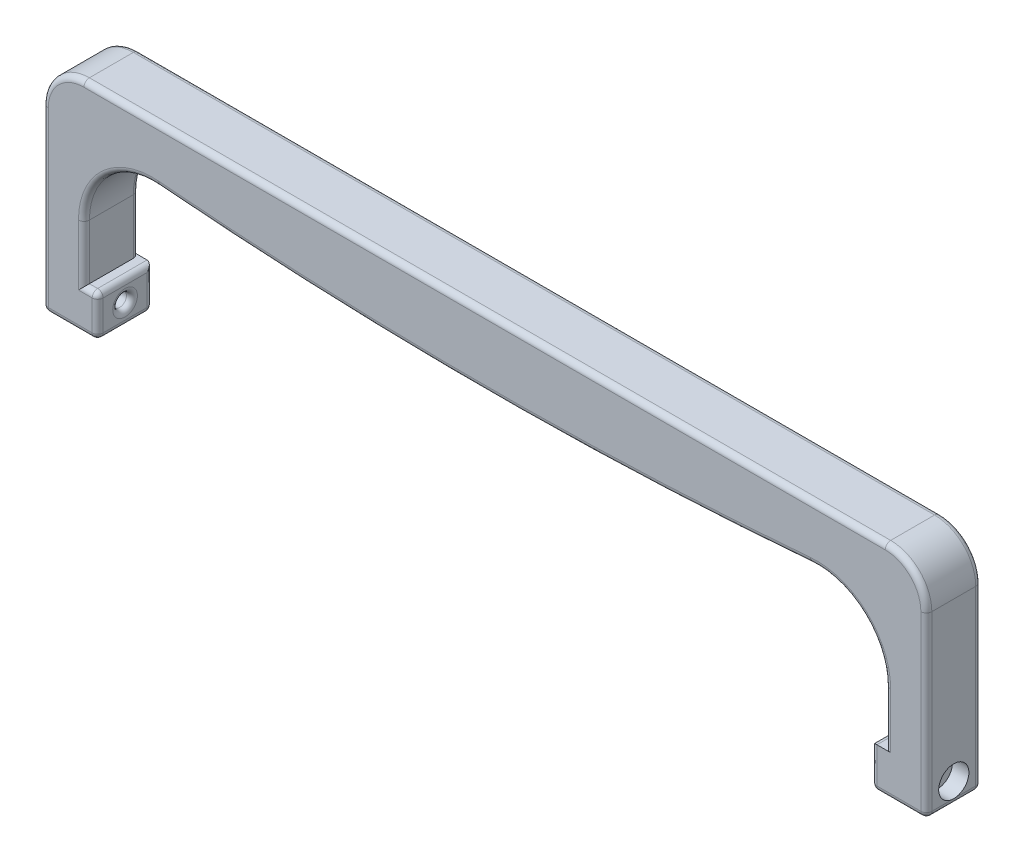
SolidWorks part; units mm, degrees
ref_plane "Ön Düzlem" through (0, 0, 0) normal (0, 0, 1) x (1, 0, 0)
ref_plane "Üst Düzlem" through (0, 0, 0) normal (0, 1, 0) x (1, 0, 0)
ref_plane "Sağ Düzlem" through (0, 0, 0) normal (1, 0, 0) x (0, 0, -1)
sketch "Sketch1" plane through (0, 0, 0) normal (0, 0, 1) x (1, 0, 0)
  line L0 (0, 0) -> (146, 0) construction
  line L1 (0, 0) -> (-146, 0) construction
  line L2 (-146, 15) -> (-146, 35.0883)
  line L3 (146, 35.0883) -> (146, 15)
  line L4 (146, 0) -> (161, 0)
  line L5 (161, 0) -> (161, 28.5778)
  line L7 (84.845, 80) -> (-146, 80)
  line L9 (-161, 28.5778) -> (-161, 0)
  line L10 (-161, 0) -> (-146, 0)
  line L11 (0, 0) -> (0, 55) construction
  line L12 (-118.9011, 60) -> (118.9011, 60) construction
  line L13 (-153.5, 0) -> (-153.5, -22.3017) construction
  line L14 (153.5, 0) -> (153.5, -21.3333) construction
  line L15 (-146, 35.0883) -> (-146, 80) construction
  line L16 (-161, 28.5778) -> (-161, 80)
  line L17 (-161, 80) -> (-146, 80)
  line L18 (84.845, 80) -> (161, 80)
  line L19 (161, 80) -> (161, 28.5778)
  line L20 (-146, 15) -> (-141, 15)
  line L21 (-141, 15) -> (-141, 0)
  line L22 (-141, 0) -> (-146, 0)
  line L23 (146, 0) -> (141, 0)
  line L24 (141, 0) -> (141, 15)
  line L25 (141, 15) -> (146, 15)
  arc A0 (-146, 35.0883) -> (-118.9011, 60) centre (-121, 35.0883) cw
  arc A1 (-118.9011, 60) -> (118.9011, 60) centre (0, 1471.2477) ccw
  arc A2 (118.9011, 60) -> (146, 35.0883) centre (121, 35.0883) cw
  dimension "D6" = 25
  dimension "D1" = 15
  dimension "D2" = 292
  dimension "D3" = 15
  dimension "D4" = 282
  dimension "D5" = 25
  dimension "D7" = 55
  dimension "D8" = 5
  dimension "D9" = 15
extrude "Boss-Extrude1" add sketch "Sketch1" along normal blind 20
fillet "Fillet7" radius 15 2 edges at (161, 80, 10) (-161, 80, 10)
sketch "Sketch5" plane through (-161, 0, 0) normal (-1, 0, 0) x (0, 0, 1)
  line L0 (10, 15) -> (10, 0) construction
  line L1 (20, 15) -> (0, 15) construction
  line L2 (20, 0) -> (0, 0) construction
  circle A0 centre (10, 7.5) radius 2.5
  dimension "D1" = 5
extrude "Cut-Extrude3" cut sketch "Sketch5" against normal through all both and the other way through all
sketch "Sketch6" plane through (-161, 0, 0) normal (-1, 0, 0) x (0, 0, 1)
  circle A0 centre (10, 7.5) radius 5.5
  dimension "D1" = 11
extrude "Cut-Extrude4" cut sketch "Sketch6" against normal blind 6
sketch "Sketch7" plane through (161, 0, 0) normal (1, 0, 0) x (0, 0, -1)
  circle A0 centre (-10, 7.5) radius 5.5 construction
  circle A1 centre (-10, 7.5) radius 5.5
extrude "Cut-Extrude5" cut sketch "Sketch7" against normal blind 6
fillet "Fillet2" radius 2 20 edges at (146, 25.0441, 20) (137.9193, 53.493, 20) (0, 55, 20) (-137.9193, 53.493, 20) (146, 25.0441, 0) (137.9193, 53.493, 0) (0, 55, 0) (-137.9193, 53.493, 0) (161, 32.5, 20) (161, 32.5, 0) (-146, 25.0441, 20) (-146, 25.0441, 0) (-161, 32.5, 0) (-161, 32.5, 20) (156.6066, 75.6066, 0) (0, 80, 0) (-156.6066, 75.6066, 0) (156.6066, 75.6066, 20) (0, 80, 20) (-156.6066, 75.6066, 20)
fillet "Fillet3" radius 2 22 edges at (150, 0, 0) (160.4142, 0, 0.5858) (161, 0, 10) (160.4142, 0, 19.4142) (-150, 0, 0) (-160.4142, 0, 0.5858) (-161, 0, 10) (-160.4142, 0, 19.4142) (141, 15, 10) (141, 7.5, 20) (141, 0, 10) (141, 7.5, 0) (141, 7.5, 7.5) (-141, 0, 10) (-141, 7.5, 20) (-141, 15, 10) (-141, 7.5, 0) (-141, 7.5, 12.5) (144.5, 15, 0) (150, 0, 20) (-150, 0, 20) (-144.5, 15, 20)
sketch "Sketch8" plane through (0, 0, -0.2) normal (0, 0, -1) x (-1, 0, 0)
  line L0 (13.5917, 71.7792) -> (12.4477, 71.7719) construction
  line L1 (12.4477, 71.7719) -> (12.4477, 70.7505) construction
  line L2 (12.4477, 70.7505) -> (11.9727, 70.2612) construction
  line L3 (11.9727, 70.2612) -> (11.6603, 69.9421) construction
  line L4 (11.6603, 69.9421) -> (10.808, 69.0802) construction
  line L5 (10.808, 69.0802) -> (9.7905, 68.0529) construction
  line L6 (9.7905, 68.0529) -> (8.6746, 66.928) construction
  line L7 (8.6746, 66.928) -> (5.8515, 64.0843) construction
  line L8 (5.8515, 64.0843) -> (7.4005, 64.1021) construction
  line L9 (7.4005, 64.1021) -> (8.367, 64.1144) construction
  line L10 (9.387, 64.425) -> (9.5549, 64.5879) construction
  line L11 (9.5549, 64.5879) -> (9.9183, 64.9488) construction
  line L12 (9.9183, 64.9488) -> (14.2886, 64.9488) construction
  line L13 (14.2886, 64.9488) -> (14.3193, 64.7681) construction
  line L14 (14.3193, 64.7681) -> (14.3331, 64.6868) construction
  line L15 (14.3331, 64.6868) -> (14.3493, 64.5913) construction
  line L16 (14.3493, 64.5913) -> (14.3653, 64.497) construction
  line L17 (14.3653, 64.497) -> (14.3784, 64.4197) construction
  line L18 (14.4551, 64.1923) -> (14.5034, 64.1326) construction
  line L19 (14.5034, 64.1326) -> (15.9518, 64.109) construction
  line L20 (15.9518, 64.109) -> (16.5084, 64.1013) construction
  line L21 (16.5084, 64.1013) -> (16.9799, 64.0975) construction
  line L22 (16.9799, 64.0975) -> (17.4007, 64.096) construction
  line L23 (17.4269, 64.1322) -> (16.7598, 67.9308) construction
  line L24 (16.7598, 67.9308) -> (16.096, 71.7092) construction
  line L25 (16.0554, 71.7873) -> (15.8667, 71.7915) construction
  line L26 (15.8667, 71.7915) -> (15.6506, 71.7939) construction
  line L27 (15.6506, 71.7939) -> (15.3964, 71.7929) construction
  line L28 (15.3964, 71.7929) -> (15.0647, 71.7899) construction
  line L29 (-30.517, 73.746) -> (-31.8816, 72.1736)
  line L30 (-31.8816, 72.1736) -> (-33.0363, 70.8497)
  line L31 (-33.0363, 70.8497) -> (-34.0807, 69.6561)
  line L32 (-34.1307, 69.6546) -> (-35.0695, 70.4608)
  line L33 (-35.0695, 70.4608) -> (-36.1096, 71.3573)
  line L34 (-36.1096, 71.3573) -> (-37.3381, 72.422)
  line L35 (-37.3381, 72.422) -> (-38.5666, 73.4878)
  line L36 (-38.5666, 73.4878) -> (-39.6068, 74.3873)
  line L37 (-39.6068, 74.3873) -> (-40.5449, 75.1969)
  line L38 (-40.651, 75.1196) -> (-40.6902, 75.0317)
  line L39 (-40.6902, 75.0317) -> (-42.2785, 71.2415)
  line L40 (-42.2785, 71.2415) -> (-44.7705, 65.2866)
  line L41 (-44.7705, 65.2866) -> (-47.6034, 58.5152)
  line L42 (-47.5883, 58.4278) -> (-46.541, 59.6299)
  line L43 (-46.541, 59.6299) -> (-45.3849, 60.9603)
  line L44 (-45.3849, 60.9603) -> (-44.0169, 62.5404)
  line L45 (-44.0169, 62.5404) -> (-42.6493, 64.1206)
  line L46 (-42.6493, 64.1206) -> (-41.4944, 65.4509)
  line L47 (-41.4944, 65.4509) -> (-40.4473, 66.6547)
  line L48 (-40.4169, 66.6556) -> (-39.4708, 65.8366)
  line L49 (-39.4708, 65.8366) -> (-38.4259, 64.9302)
  line L50 (-38.4259, 64.9302) -> (-37.1889, 63.8535)
  line L51 (-37.1889, 63.8535) -> (-35.6006, 62.472)
  line L52 (-35.6006, 62.472) -> (-34.6607, 61.6627)
  line L53 (-34.6607, 61.6627) -> (-33.9717, 61.0753)
  line L54 (-33.9037, 61.1285) -> (-30.4157, 69.4499)
  line L55 (-30.4157, 69.4499) -> (-26.9268, 77.7738)
  line L56 (-26.957, 77.8394) -> (-28.0011, 76.6423)
  line L57 (-28.0011, 76.6423) -> (-29.1532, 75.3185)
  line L58 (-30.517, 73.746) -> (-31.8816, 72.1736)
  line L59 (-31.8816, 72.1736) -> (-33.0363, 70.8497)
  line L60 (-33.0363, 70.8497) -> (-34.0807, 69.6561)
  line L61 (-34.1307, 69.6546) -> (-35.0695, 70.4608)
  line L62 (-35.0695, 70.4608) -> (-36.1096, 71.3573)
  line L63 (-36.1096, 71.3573) -> (-37.3381, 72.422)
  line L64 (-37.3381, 72.422) -> (-38.5666, 73.4878)
  line L65 (-38.5666, 73.4878) -> (-39.6068, 74.3873)
  line L66 (-39.6068, 74.3873) -> (-40.5449, 75.1969)
  line L67 (-40.651, 75.1196) -> (-40.6902, 75.0317)
  line L68 (-40.6902, 75.0317) -> (-42.2785, 71.2415)
  line L69 (-42.2785, 71.2415) -> (-44.7705, 65.2866)
  line L70 (-44.7705, 65.2866) -> (-47.6034, 58.5152)
  line L71 (-47.5883, 58.4278) -> (-46.541, 59.6299)
  line L72 (-46.541, 59.6299) -> (-45.3849, 60.9603)
  line L73 (-45.3849, 60.9603) -> (-44.0169, 62.5404)
  line L74 (-44.0169, 62.5404) -> (-42.6493, 64.1206)
  line L75 (-42.6493, 64.1206) -> (-41.4944, 65.4509)
  line L76 (-41.4944, 65.4509) -> (-40.4473, 66.6547)
  line L77 (-40.4169, 66.6556) -> (-39.4708, 65.8366)
  line L78 (-39.4708, 65.8366) -> (-38.4259, 64.9302)
  line L79 (-38.4259, 64.9302) -> (-37.1889, 63.8535)
  line L80 (-37.1889, 63.8535) -> (-35.6006, 62.472)
  line L81 (-35.6006, 62.472) -> (-34.6607, 61.6627)
  line L82 (-34.6607, 61.6627) -> (-33.9717, 61.0753)
  line L83 (-33.9037, 61.1285) -> (-30.4157, 69.4499)
  line L84 (-30.4157, 69.4499) -> (-26.9268, 77.7738)
  line L85 (-26.957, 77.8394) -> (-28.0011, 76.6423)
  line L86 (-28.0011, 76.6423) -> (-29.1532, 75.3185)
  line L87 (15.0647, 71.7899) -> (14.5937, 71.7862) construction
  line L88 (14.5937, 71.7862) -> (14.0781, 71.7825) construction
  line L89 (-3.5813, 71.7993) -> (-3.5813, 70.2877) construction
  line L90 (-3.5813, 70.2877) -> (-4.878, 67.2503) construction
  line L91 (-4.878, 67.2503) -> (-5.3764, 66.0823) construction
  line L92 (-5.3764, 66.0823) -> (-5.799, 65.0911) construction
  line L93 (-5.799, 65.0911) -> (-6.1772, 64.2033) construction
  line L94 (-6.1772, 64.2033) -> (-6.1925, 64.165) construction
  line L95 (-5.772, 64.121) -> (-5.0497, 64.1248) construction
  line L96 (-5.0497, 64.1248) -> (-3.8891, 64.1326) construction
  line L97 (-3.8891, 64.1326) -> (-3.7553, 64.2034) construction
  line L98 (-3.4372, 64.4881) -> (-3.4095, 64.5458) construction
  line L99 (-3.4095, 64.5458) -> (-3.3182, 64.7528) construction
  line L100 (-3.3182, 64.7528) -> (-3.2109, 64.9986) construction
  line L101 (-25.1946, 71.8011) -> (-25.2279, 70.3122)
  line L102 (-25.2279, 70.3122) -> (-26.5297, 67.2491)
  line L103 (-26.5297, 67.2491) -> (-27.0298, 66.0723)
  line L104 (-27.0298, 66.0723) -> (-27.4531, 65.0758)
  line L105 (-27.4531, 65.0758) -> (-27.8337, 64.1795)
  line L106 (-27.8337, 64.1795) -> (-27.8452, 64.1516)
  line L107 (-27.8323, 64.1321) -> (-27.6149, 64.1255)
  line L108 (-27.6149, 64.1255) -> (-27.2782, 64.1221)
  line L109 (-27.2782, 64.1221) -> (-26.6314, 64.1249)
  line L110 (-26.6314, 64.1249) -> (-25.4039, 64.1326)
  line L111 (-25.4039, 64.1326) -> (-25.2507, 64.2078)
  line L112 (-24.9429, 64.4922) -> (-24.7356, 64.9493)
  line L113 (-24.7356, 64.9493) -> (-24.454, 65.5884)
  line L114 (-24.454, 65.5884) -> (-24.0391, 66.5517)
  line L115 (-24.0391, 66.5517) -> (-23.6994, 67.3423)
  line L116 (-23.6994, 67.3423) -> (-23.4108, 68.008)
  line L117 (-23.4108, 68.008) -> (-23.1493, 68.608)
  line L118 (-23.1311, 68.6086) -> (-22.8358, 67.9695)
  line L119 (-22.8358, 67.9695) -> (-22.51, 67.2606)
  line L120 (-22.51, 67.2606) -> (-22.126, 66.4185)
  line L121 (-22.126, 66.4185) -> (-21.6201, 65.3102)
  line L122 (-21.6201, 65.3102) -> (-21.3228, 64.6737)
  line L123 (-21.3228, 64.6737) -> (-21.1139, 64.2395)
  line L124 (-20.5132, 64.1339) -> (-19.839, 64.1326)
  line L125 (-19.839, 64.1326) -> (-18.6872, 64.1326)
  line L126 (-18.6872, 64.1326) -> (-18.5174, 64.2246)
  line L127 (-18.2242, 64.5066) -> (-16.7137, 68.0459)
  line L128 (-16.7137, 68.0459) -> (-15.2225, 71.542)
  line L129 (-15.5907, 71.7982) -> (-16.3489, 71.7941)
  line L130 (-16.3489, 71.7941) -> (-17.5633, 71.7859)
  line L131 (-17.5633, 71.7859) -> (-17.6955, 71.7203)
  line L132 (-18.2461, 70.9566) -> (-18.8059, 69.6317)
  line L133 (-18.8059, 69.6317) -> (-19.0984, 68.9368)
  line L134 (-19.0984, 68.9368) -> (-19.3491, 68.3462)
  line L135 (-19.3491, 68.3462) -> (-19.5732, 67.821)
  line L136 (-19.8037, 67.8199) -> (-20.0598, 68.3812)
  line L137 (-20.0598, 68.3812) -> (-20.3462, 69.0103)
  line L138 (-20.3462, 69.0103) -> (-20.6822, 69.7509)
  line L139 (-20.6822, 69.7509) -> (-21.1251, 70.7235)
  line L140 (-21.1251, 70.7235) -> (-21.3873, 71.2842)
  line L141 (-21.3873, 71.2842) -> (-21.5702, 71.6613)
  line L142 (-22.3255, 71.7876) -> (-23.4481, 71.7935)
  line L143 (-23.4481, 71.7935) -> (-25.1946, 71.8011)
  line L144 (-25.1946, 71.8011) -> (-25.2279, 70.3122)
  line L145 (-25.2279, 70.3122) -> (-26.5297, 67.2491)
  line L146 (-26.5297, 67.2491) -> (-27.0298, 66.0723)
  line L147 (-27.0298, 66.0723) -> (-27.4531, 65.0758)
  line L148 (-27.4531, 65.0758) -> (-27.8337, 64.1795)
  line L149 (-27.8337, 64.1795) -> (-27.8452, 64.1516)
  line L150 (-27.8323, 64.1321) -> (-27.6149, 64.1255)
  line L151 (-27.6149, 64.1255) -> (-27.2782, 64.1221)
  line L152 (-27.2782, 64.1221) -> (-26.6314, 64.1249)
  line L153 (-26.6314, 64.1249) -> (-25.4039, 64.1326)
  line L154 (-25.4039, 64.1326) -> (-25.2507, 64.2078)
  line L155 (-24.9429, 64.4922) -> (-24.7356, 64.9493)
  line L156 (-24.7356, 64.9493) -> (-24.454, 65.5884)
  line L157 (-24.454, 65.5884) -> (-24.0391, 66.5517)
  line L158 (-24.0391, 66.5517) -> (-23.6994, 67.3423)
  line L159 (-23.6994, 67.3423) -> (-23.4108, 68.008)
  line L160 (-23.4108, 68.008) -> (-23.1493, 68.608)
  line L161 (-23.1311, 68.6086) -> (-22.8358, 67.9695)
  line L162 (-22.8358, 67.9695) -> (-22.51, 67.2606)
  line L163 (-22.51, 67.2606) -> (-22.126, 66.4185)
  line L164 (-22.126, 66.4185) -> (-21.6201, 65.3102)
  line L165 (-21.6201, 65.3102) -> (-21.3228, 64.6737)
  line L166 (-21.3228, 64.6737) -> (-21.1139, 64.2395)
  line L167 (-20.5132, 64.1339) -> (-19.839, 64.1326)
  line L168 (-19.839, 64.1326) -> (-18.6872, 64.1326)
  line L169 (-18.6872, 64.1326) -> (-18.5174, 64.2246)
  line L170 (-18.2242, 64.5066) -> (-16.7137, 68.0459)
  line L171 (-16.7137, 68.0459) -> (-15.2225, 71.542)
  line L172 (-15.5907, 71.7982) -> (-16.3489, 71.7941)
  line L173 (-16.3489, 71.7941) -> (-17.5633, 71.7859)
  line L174 (-17.5633, 71.7859) -> (-17.6955, 71.7203)
  line L175 (-18.2461, 70.9566) -> (-18.8059, 69.6317)
  line L176 (-18.8059, 69.6317) -> (-19.0984, 68.9368)
  line L177 (-19.0984, 68.9368) -> (-19.3491, 68.3462)
  line L178 (-19.3491, 68.3462) -> (-19.5732, 67.821)
  line L179 (-19.8037, 67.8199) -> (-20.0598, 68.3812)
  line L180 (-20.0598, 68.3812) -> (-20.3462, 69.0103)
  line L181 (-20.3462, 69.0103) -> (-20.6822, 69.7509)
  line L182 (-20.6822, 69.7509) -> (-21.1251, 70.7235)
  line L183 (-21.1251, 70.7235) -> (-21.3873, 71.2842)
  line L184 (-21.3873, 71.2842) -> (-21.5702, 71.6613)
  line L185 (-22.3255, 71.7876) -> (-23.4481, 71.7935)
  line L186 (-23.4481, 71.7935) -> (-25.1946, 71.8011)
  line L187 (-3.2109, 64.9986) -> (-3.0917, 65.2745) construction
  line L188 (-3.0917, 65.2745) -> (-2.902, 65.7249) construction
  line L189 (-2.7144, 66.2822) -> (-2.5766, 66.8086) construction
  line L190 (-2.5766, 66.8086) -> (-2.3647, 67.6381) construction
  line L191 (-2.3647, 67.6381) -> (-2.3424, 67.4909) construction
  line L192 (-2.3424, 67.4909) -> (-2.1759, 66.4174) construction
  line L193 (-2.1759, 66.4174) -> (-2.001, 65.3432) construction
  line L194 (-2.001, 65.3432) -> (-1.8277, 64.3062) construction
  line L195 (-1.1942, 64.1215) -> (-0.3702, 64.1243) construction
  line L196 (-0.3702, 64.1243) -> (0.4121, 64.1309) construction
  line L197 (1.039, 64.263) -> (1.3895, 64.5936) construction
  line L198 (1.3895, 64.5936) -> (1.8582, 65.0459) construction
  line L199 (1.8582, 65.0459) -> (2.5199, 65.6965) construction
  line L200 (2.5199, 65.6965) -> (3.0795, 66.2488) construction
  line L201 (3.0795, 66.2488) -> (3.5516, 66.7128) construction
  line L202 (3.5516, 66.7128) -> (3.9794, 67.1323) construction
  line L203 (3.9853, 67.1271) -> (3.8229, 66.7398) construction
  line L204 (3.8229, 66.7398) -> (3.6425, 66.3114) construction
  line L205 (3.6425, 66.3114) -> (3.4271, 65.8037) construction
  line L206 (3.4271, 65.8037) -> (3.2103, 65.2905) construction
  line L207 (3.2103, 65.2905) -> (3.0253, 64.8447) construction
  line L208 (3.0253, 64.8447) -> (2.8673, 64.4584) construction
  line L209 (3.5576, 64.1231) -> (4.1957, 64.1256) construction
  line L210 (4.1957, 64.1256) -> (5.338, 64.1326) construction
  line L211 (5.338, 64.1326) -> (6.9661, 67.9543) construction
  line L212 (6.9661, 67.9543) -> (7.5905, 69.4206) construction
  line L213 (7.5905, 69.4206) -> (8.116, 70.6572) construction
  line L214 (8.116, 70.6572) -> (8.5922, 71.7787) construction
  line L215 (8.589, 71.7943) -> (8.1915, 71.7958) construction
  line L216 (8.1915, 71.7958) -> (7.7488, 71.7961) construction
  line L217 (7.7488, 71.7961) -> (7.2229, 71.7939) construction
  line L218 (7.2229, 71.7939) -> (5.8515, 71.7859) construction
  line L219 (5.8515, 71.7859) -> (5.7177, 71.7216) construction
  line L220 (5.5902, 71.6332) -> (5.1182, 71.1787) construction
  line L221 (5.1182, 71.1787) -> (4.4076, 70.4805) construction
  line L222 (4.4076, 70.4805) -> (3.1287, 69.2066) construction
  line L223 (3.1287, 69.2066) -> (2.1872, 68.2687) construction
  line L224 (2.1872, 68.2687) -> (1.3947, 67.4836) construction
  line L225 (1.3947, 67.4836) -> (0.6812, 66.7793) construction
  line L226 (0.6716, 66.804) -> (0.5984, 67.2298) construction
  line L227 (0.5984, 67.2298) -> (0.516, 67.7065) construction
  line L228 (0.516, 67.7065) -> (0.418, 68.2674) construction
  line L229 (0.418, 68.2674) -> (0.2912, 69.0089) construction
  line L230 (0.2912, 69.0089) -> (0.1961, 69.6063) construction
  line L231 (0.1961, 69.6063) -> (0.1213, 70.132) construction
  line L232 (0.1213, 70.132) -> (0.0574, 70.6486) construction
  line L233 (0.0574, 70.6486) -> (0.016, 71.0105) construction
  line L234 (0.016, 71.0105) -> (-0.0215, 71.334) construction
  line L235 (-0.0215, 71.334) -> (-0.0534, 71.6066) construction
  line L236 (-0.0534, 71.6066) -> (-0.0635, 71.6855) construction
  line L237 (-0.0635, 71.6855) -> (-0.0791, 71.7993) construction
  line L238 (-0.0791, 71.7993) -> (-3.5813, 71.7993) construction
  line L239 (13.5917, 71.7792) -> (12.4477, 71.7719)
  line L240 (12.4477, 71.7719) -> (12.4477, 70.7505)
  line L241 (12.4477, 70.7505) -> (11.9727, 70.2612)
  line L242 (11.9727, 70.2612) -> (11.6603, 69.9421)
  line L243 (11.6603, 69.9421) -> (10.808, 69.0802)
  line L244 (10.808, 69.0802) -> (9.7905, 68.0529)
  line L245 (9.7905, 68.0529) -> (8.6746, 66.928)
  line L246 (8.6746, 66.928) -> (5.8515, 64.0843)
  line L247 (5.8515, 64.0843) -> (7.4005, 64.1021)
  line L248 (7.4005, 64.1021) -> (8.367, 64.1144)
  line L249 (9.387, 64.425) -> (9.5549, 64.5879)
  line L250 (9.5549, 64.5879) -> (9.9183, 64.9488)
  line L251 (9.9183, 64.9488) -> (14.2886, 64.9488)
  line L252 (14.2886, 64.9488) -> (14.3193, 64.7681)
  line L253 (14.3193, 64.7681) -> (14.3331, 64.6868)
  line L254 (14.3331, 64.6868) -> (14.3493, 64.5913)
  line L255 (14.3493, 64.5913) -> (14.3653, 64.497)
  line L256 (14.3653, 64.497) -> (14.3784, 64.4197)
  line L257 (14.4551, 64.1923) -> (14.5034, 64.1326)
  line L258 (14.5034, 64.1326) -> (15.9518, 64.109)
  line L259 (15.9518, 64.109) -> (16.5084, 64.1013)
  line L260 (16.5084, 64.1013) -> (16.9799, 64.0975)
  line L261 (16.9799, 64.0975) -> (17.4007, 64.096)
  line L262 (17.4269, 64.1322) -> (16.7598, 67.9308)
  line L263 (16.7598, 67.9308) -> (16.096, 71.7092)
  line L264 (16.0554, 71.7873) -> (15.8667, 71.7915)
  line L265 (15.8667, 71.7915) -> (15.6506, 71.7939)
  line L266 (15.6506, 71.7939) -> (15.3964, 71.7929)
  line L267 (15.3964, 71.7929) -> (15.0647, 71.7899)
  line L268 (15.0647, 71.7899) -> (14.5937, 71.7862)
  line L269 (14.5937, 71.7862) -> (14.0781, 71.7825)
  line L270 (-3.5813, 71.7993) -> (-3.5813, 70.2877)
  line L271 (-3.5813, 70.2877) -> (-4.878, 67.2503)
  line L272 (-4.878, 67.2503) -> (-5.3764, 66.0823)
  line L273 (-5.3764, 66.0823) -> (-5.799, 65.0911)
  line L274 (-5.799, 65.0911) -> (-6.1772, 64.2033)
  line L275 (-6.1772, 64.2033) -> (-6.1925, 64.165)
  line L276 (-5.772, 64.121) -> (-5.0497, 64.1248)
  line L277 (-5.0497, 64.1248) -> (-3.8891, 64.1326)
  line L278 (-3.8891, 64.1326) -> (-3.7553, 64.2034)
  line L279 (-3.4372, 64.4881) -> (-3.4095, 64.5458)
  line L280 (-3.4095, 64.5458) -> (-3.3182, 64.7528)
  line L281 (-3.3182, 64.7528) -> (-3.2109, 64.9986)
  line L282 (-3.2109, 64.9986) -> (-3.0917, 65.2745)
  line L283 (-3.0917, 65.2745) -> (-2.902, 65.7249)
  line L284 (-2.7144, 66.2822) -> (-2.5766, 66.8086)
  line L285 (-2.5766, 66.8086) -> (-2.3647, 67.6381)
  line L286 (-2.3647, 67.6381) -> (-2.3424, 67.4909)
  line L287 (-2.3424, 67.4909) -> (-2.1759, 66.4174)
  line L288 (-2.1759, 66.4174) -> (-2.001, 65.3432)
  line L289 (-2.001, 65.3432) -> (-1.8277, 64.3062)
  line L290 (-1.1942, 64.1215) -> (-0.3702, 64.1243)
  line L291 (-0.3702, 64.1243) -> (0.4121, 64.1309)
  line L292 (1.039, 64.263) -> (1.3895, 64.5936)
  line L293 (1.3895, 64.5936) -> (1.8582, 65.0459)
  line L294 (1.8582, 65.0459) -> (2.5199, 65.6965)
  line L295 (2.5199, 65.6965) -> (3.0795, 66.2488)
  line L296 (3.0795, 66.2488) -> (3.5516, 66.7128)
  line L297 (3.5516, 66.7128) -> (3.9794, 67.1323)
  line L298 (3.9853, 67.1271) -> (3.8229, 66.7398)
  line L299 (3.8229, 66.7398) -> (3.6425, 66.3114)
  line L300 (3.6425, 66.3114) -> (3.4271, 65.8037)
  line L301 (3.4271, 65.8037) -> (3.2103, 65.2905)
  line L302 (3.2103, 65.2905) -> (3.0253, 64.8447)
  line L303 (3.0253, 64.8447) -> (2.8673, 64.4584)
  line L304 (3.5576, 64.1231) -> (4.1957, 64.1256)
  line L305 (4.1957, 64.1256) -> (5.338, 64.1326)
  line L306 (5.338, 64.1326) -> (6.9661, 67.9543)
  line L307 (6.9661, 67.9543) -> (7.5905, 69.4206)
  line L308 (7.5905, 69.4206) -> (8.116, 70.6572)
  line L309 (8.116, 70.6572) -> (8.5922, 71.7787)
  line L310 (8.589, 71.7943) -> (8.1915, 71.7958)
  line L311 (8.1915, 71.7958) -> (7.7488, 71.7961)
  line L312 (7.7488, 71.7961) -> (7.2229, 71.7939)
  line L313 (7.2229, 71.7939) -> (5.8515, 71.7859)
  line L314 (5.8515, 71.7859) -> (5.7177, 71.7216)
  line L315 (5.5902, 71.6332) -> (5.1182, 71.1787)
  line L316 (5.1182, 71.1787) -> (4.4076, 70.4805)
  line L317 (4.4076, 70.4805) -> (3.1287, 69.2066)
  line L318 (3.1287, 69.2066) -> (2.1872, 68.2687)
  line L319 (2.1872, 68.2687) -> (1.3947, 67.4836)
  line L320 (1.3947, 67.4836) -> (0.6812, 66.7793)
  line L321 (0.6716, 66.804) -> (0.5984, 67.2298)
  line L322 (0.5984, 67.2298) -> (0.516, 67.7065)
  line L323 (0.516, 67.7065) -> (0.418, 68.2674)
  line L324 (0.418, 68.2674) -> (0.2912, 69.0089)
  line L325 (0.2912, 69.0089) -> (0.1961, 69.6063)
  line L326 (0.1961, 69.6063) -> (0.1213, 70.132)
  line L327 (0.1213, 70.132) -> (0.0574, 70.6486)
  line L328 (0.0574, 70.6486) -> (0.016, 71.0105)
  line L329 (0.016, 71.0105) -> (-0.0215, 71.334)
  line L330 (-0.0215, 71.334) -> (-0.0534, 71.6066)
  line L331 (-0.0534, 71.6066) -> (-0.0635, 71.6855)
  line L332 (-0.0635, 71.6855) -> (-0.0791, 71.7993)
  line L333 (-0.0791, 71.7993) -> (-3.5813, 71.7993)
  line L334 (11.7959, 66.7669) -> (14.007, 66.7885)
  line L335 (14.007, 66.7885) -> (13.6567, 68.706)
  line L336 (13.6567, 68.706) -> (11.7959, 66.7669)
  line L337 (31.1127, 71.716) -> (31.0101, 71.4717) construction
  line L338 (31.0101, 71.4717) -> (30.8919, 71.1891) construction
  line L339 (30.8919, 71.1891) -> (30.7564, 70.8627) construction
  line L340 (30.7564, 70.8627) -> (30.6188, 70.5305) construction
  line L341 (30.6188, 70.5305) -> (30.494, 70.2299) construction
  line L342 (30.494, 70.2299) -> (30.389, 69.9778) construction
  line L343 (30.389, 69.9778) -> (30.3528, 69.8924) construction
  line L344 (30.3528, 69.8924) -> (30.2981, 69.765) construction
  line L345 (30.2981, 69.765) -> (33.0892, 69.7789) construction
  line L346 (33.0892, 69.7789) -> (33.5254, 70.769) construction
  line L347 (33.5254, 70.769) -> (33.6926, 71.1501) construction
  line L348 (33.6926, 71.1501) -> (33.8335, 71.4742) construction
  line L349 (33.8335, 71.4742) -> (33.9586, 71.7637) construction
  line L350 (33.9541, 71.7874) -> (33.55, 71.7934) construction
  line L351 (20.5107, 71.7737) -> (20.48, 70.2553)
  line L352 (20.48, 70.2553) -> (19.1898, 67.2207)
  line L353 (19.1898, 67.2207) -> (18.6941, 66.0538)
  line L354 (18.6941, 66.0538) -> (18.2747, 65.0636)
  line L355 (18.2747, 65.0636) -> (17.8995, 64.1761)
  line L356 (17.9105, 64.1065) -> (18.3839, 64.099)
  line L357 (18.3839, 64.099) -> (19.1945, 64.095)
  line L358 (19.1945, 64.095) -> (21.4558, 64.099)
  line L359 (21.4558, 64.099) -> (25.0382, 64.1069)
  line L360 (25.0382, 64.1069) -> (25.3109, 64.1792)
  line L361 (27.8496, 66.2627) -> (28.5848, 68.0031)
  line L362 (28.5848, 68.0031) -> (29.34, 69.7964)
  line L363 (28.4498, 71.6967) -> (28.2493, 71.7585)
  line L364 (28.2493, 71.7585) -> (20.5107, 71.7737)
  line L365 (20.5107, 71.7737) -> (20.48, 70.2553)
  line L366 (20.48, 70.2553) -> (19.1898, 67.2207)
  line L367 (19.1898, 67.2207) -> (18.6941, 66.0538)
  line L368 (18.6941, 66.0538) -> (18.2747, 65.0636)
  line L369 (18.2747, 65.0636) -> (17.8995, 64.1761)
  line L370 (17.9105, 64.1065) -> (18.3839, 64.099)
  line L371 (18.3839, 64.099) -> (19.1945, 64.095)
  line L372 (19.1945, 64.095) -> (21.4558, 64.099)
  line L373 (21.4558, 64.099) -> (25.0382, 64.1069)
  line L374 (25.0382, 64.1069) -> (25.3109, 64.1792)
  line L375 (27.8496, 66.2627) -> (28.5848, 68.0031)
  line L376 (28.5848, 68.0031) -> (29.34, 69.7964)
  line L377 (28.4498, 71.6967) -> (28.2493, 71.7585)
  line L378 (28.2493, 71.7585) -> (20.5107, 71.7737)
  line L379 (33.55, 71.7934) -> (33.0969, 71.7978) construction
  line L380 (33.0969, 71.7978) -> (32.5586, 71.7993) construction
  line L381 (32.5586, 71.7993) -> (31.697, 71.7982) construction
  line L382 (30.0275, 69.0163) -> (30.0037, 68.956) construction
  line L383 (30.0037, 68.956) -> (29.9841, 68.9084) construction
  line L384 (29.9841, 68.9084) -> (29.6944, 68.2257) construction
  line L385 (29.6944, 68.2257) -> (29.3676, 67.4563) construction
  line L386 (29.3676, 67.4563) -> (28.9841, 66.5544) construction
  line L387 (28.9841, 66.5544) -> (28.6015, 65.6523) construction
  line L388 (28.6015, 65.6523) -> (28.277, 64.8825) construction
  line L389 (28.277, 64.8825) -> (27.9901, 64.1989) construction
  line L390 (27.9749, 64.1509) -> (27.9614, 64.089) construction
  line L391 (27.9614, 64.089) -> (30.3633, 64.1058) construction
  line L392 (30.3633, 64.1058) -> (30.5273, 64.1816) construction
  line L393 (31.1381, 65.0528) -> (31.8509, 66.7022) construction
  line L394 (31.8509, 66.7022) -> (32.2224, 67.5662) construction
  line L395 (32.2224, 67.5662) -> (32.5375, 68.2991) construction
  line L396 (32.5375, 68.2991) -> (32.8197, 68.9559) construction
  line L397 (32.8197, 68.9559) -> (32.8309, 68.9828) construction
  line L398 (32.8185, 69.0018) -> (32.5559, 69.0095) construction
  line L399 (32.5559, 69.0095) -> (32.163, 69.0149) construction
  line L400 (32.163, 69.0149) -> (31.4359, 69.0163) construction
  line L401 (31.4359, 69.0163) -> (30.0275, 69.0163) construction
  line L402 (31.1127, 71.716) -> (31.0101, 71.4717)
  line L403 (31.0101, 71.4717) -> (30.8919, 71.1891)
  line L404 (30.8919, 71.1891) -> (30.7564, 70.8627)
  line L405 (30.7564, 70.8627) -> (30.6188, 70.5305)
  line L406 (30.6188, 70.5305) -> (30.494, 70.2299)
  line L407 (30.494, 70.2299) -> (30.389, 69.9778)
  line L408 (30.389, 69.9778) -> (30.3528, 69.8924)
  line L409 (30.3528, 69.8924) -> (30.2981, 69.765)
  line L410 (30.2981, 69.765) -> (33.0892, 69.7789)
  line L411 (33.0892, 69.7789) -> (33.5254, 70.769)
  line L412 (33.5254, 70.769) -> (33.6926, 71.1501)
  line L413 (33.6926, 71.1501) -> (33.8335, 71.4742)
  line L414 (33.8335, 71.4742) -> (33.9586, 71.7637)
  line L415 (33.9541, 71.7874) -> (33.55, 71.7934)
  line L416 (33.55, 71.7934) -> (33.0969, 71.7978)
  line L417 (33.0969, 71.7978) -> (32.5586, 71.7993)
  line L418 (32.5586, 71.7993) -> (31.697, 71.7982)
  line L419 (30.0275, 69.0163) -> (30.0037, 68.956)
  line L420 (30.0037, 68.956) -> (29.9841, 68.9084)
  line L421 (29.9841, 68.9084) -> (29.6944, 68.2257)
  line L422 (29.6944, 68.2257) -> (29.3676, 67.4563)
  line L423 (29.3676, 67.4563) -> (28.9841, 66.5544)
  line L424 (28.9841, 66.5544) -> (28.6015, 65.6523)
  line L425 (28.6015, 65.6523) -> (28.277, 64.8825)
  line L426 (28.277, 64.8825) -> (27.9901, 64.1989)
  line L427 (27.9749, 64.1509) -> (27.9614, 64.089)
  line L428 (27.9614, 64.089) -> (30.3633, 64.1058)
  line L429 (30.3633, 64.1058) -> (30.5273, 64.1816)
  line L430 (31.1381, 65.0528) -> (31.8509, 66.7022)
  line L431 (31.8509, 66.7022) -> (32.2224, 67.5662)
  line L432 (32.2224, 67.5662) -> (32.5375, 68.2991)
  line L433 (32.5375, 68.2991) -> (32.8197, 68.9559)
  line L434 (32.8197, 68.9559) -> (32.8309, 68.9828)
  line L435 (32.8185, 69.0018) -> (32.5559, 69.0095)
  line L436 (32.5559, 69.0095) -> (32.163, 69.0149)
  line L437 (32.163, 69.0149) -> (31.4359, 69.0163)
  line L438 (31.4359, 69.0163) -> (30.0275, 69.0163)
  line L439 (21.9151, 66.119) -> (24.6899, 66.1137)
  line L440 (24.6899, 66.1137) -> (24.943, 66.2197)
  line L441 (24.943, 66.2197) -> (26.4633, 69.6104)
  line L442 (26.4633, 69.6104) -> (26.3013, 69.7765)
  line L443 (26.3013, 69.7765) -> (23.0686, 69.7923)
  line L444 (23.0686, 69.7923) -> (21.6091, 66.3272)
  line L445 (21.6091, 66.3272) -> (21.6889, 66.1423)
  line L446 (21.6889, 66.1423) -> (21.9151, 66.119)
  line L447 (35.7246, 66.0912) -> (38.2307, 66.073)
  line L448 (38.2307, 66.073) -> (39.2248, 68.4463)
  line L449 (39.2248, 68.4463) -> (40.361, 67.0297)
  line L450 (40.361, 67.0297) -> (41.4089, 69.5268)
  line L451 (41.4089, 69.5268) -> (41.3324, 69.769)
  line L452 (41.3324, 69.769) -> (36.9646, 69.7923)
  line L453 (36.9646, 69.7923) -> (35.4959, 66.2594)
  line L454 (35.4959, 66.2594) -> (35.7246, 66.0912)
  line L455 (-13.5976, 66.3764) -> (-12.1646, 69.7923)
  line L456 (-12.1646, 69.7923) -> (-7.8655, 69.7761)
  line L457 (-7.8655, 69.7761) -> (-7.7361, 69.5699)
  line L458 (-7.7361, 69.5699) -> (-9.0708, 66.422)
  line L459 (-9.0708, 66.422) -> (-9.4391, 66.1467)
  line L460 (-9.4391, 66.1467) -> (-13.4849, 66.1262)
  line L461 (-13.4849, 66.1262) -> (-13.5976, 66.3764)
  line L470 (34.0021, 69.3718) -> (33.4015, 67.9726)
  line L471 (33.4015, 67.9726) -> (33.0684, 67.1868)
  line L472 (33.0684, 67.1868) -> (32.7805, 66.4986)
  line L473 (32.7805, 66.4986) -> (32.5363, 65.9079)
  line L474 (33.9889, 64.081) -> (34.654, 64.0728)
  line L475 (34.654, 64.0728) -> (35.528, 64.0669)
  line L476 (35.528, 64.0669) -> (36.7006, 64.0648)
  line L477 (36.7006, 64.0648) -> (39.3814, 64.0639)
  line L478 (39.3814, 64.0639) -> (40.1687, 63.0333)
  line L479 (40.1687, 63.0333) -> (40.4717, 62.6375)
  line L480 (40.4717, 62.6375) -> (40.7293, 62.3026)
  line L481 (40.7293, 62.3026) -> (40.9608, 62.0028)
  line L482 (40.9872, 61.998) -> (41.5253, 63.2658)
  line L483 (41.5253, 63.2658) -> (42.038, 64.476)
  line L484 (42.0041, 64.8145) -> (41.905, 64.9495)
  line L485 (41.905, 64.9495) -> (42.1819, 65.2395)
  line L486 (42.7337, 66.0299) -> (43.5106, 67.8299)
  line L487 (43.5106, 67.8299) -> (44.2647, 69.5876)
  line L488 (43.3643, 71.7523) -> (43.1545, 71.8115)
  line L489 (43.1545, 71.8115) -> (40.2109, 71.8158)
  line L490 (40.2109, 71.8158) -> (39.0683, 71.8157)
  line L491 (39.0683, 71.8157) -> (38.0731, 71.8119)
  line L492 (38.0731, 71.8119) -> (37.2183, 71.806)
  line L493 (34.0021, 69.3718) -> (33.4015, 67.9726)
  line L494 (33.4015, 67.9726) -> (33.0684, 67.1868)
  line L495 (33.0684, 67.1868) -> (32.7805, 66.4986)
  line L496 (32.7805, 66.4986) -> (32.5363, 65.9079)
  line L497 (33.9889, 64.081) -> (34.654, 64.0728)
  line L498 (34.654, 64.0728) -> (35.528, 64.0669)
  line L499 (35.528, 64.0669) -> (36.7006, 64.0648)
  line L500 (36.7006, 64.0648) -> (39.3814, 64.0639)
  line L501 (39.3814, 64.0639) -> (40.1687, 63.0333)
  line L502 (40.1687, 63.0333) -> (40.4717, 62.6375)
  line L503 (40.4717, 62.6375) -> (40.7293, 62.3026)
  line L504 (40.7293, 62.3026) -> (40.9608, 62.0028)
  line L505 (40.9872, 61.998) -> (41.5253, 63.2658)
  line L506 (41.5253, 63.2658) -> (42.038, 64.476)
  line L507 (42.0041, 64.8145) -> (41.905, 64.9495)
  line L508 (41.905, 64.9495) -> (42.1819, 65.2395)
  line L509 (42.7337, 66.0299) -> (43.5106, 67.8299)
  line L510 (43.5106, 67.8299) -> (44.2647, 69.5876)
  line L511 (43.3643, 71.7523) -> (43.1545, 71.8115)
  line L512 (43.1545, 71.8115) -> (40.2109, 71.8158)
  line L513 (40.2109, 71.8158) -> (39.0683, 71.8157)
  line L514 (39.0683, 71.8157) -> (38.0731, 71.8119)
  line L515 (38.0731, 71.8119) -> (37.2183, 71.806)
  line L516 (-14.9281, 69.8642) -> (-15.1723, 69.294)
  line L517 (-15.1723, 69.294) -> (-15.4556, 68.629)
  line L518 (-15.4556, 68.629) -> (-15.7789, 67.8656)
  line L519 (-15.7789, 67.8656) -> (-16.3838, 66.4229)
  line L520 (-14.9745, 64.113) -> (-14.2012, 64.107)
  line L521 (-14.2012, 64.107) -> (-12.2916, 64.1058)
  line L522 (-12.2916, 64.1058) -> (-9.1607, 64.1058)
  line L523 (-9.1607, 64.1058) -> (-8.8727, 64.181)
  line L524 (-6.449, 66.0116) -> (-5.6577, 67.8497)
  line L525 (-5.6577, 67.8497) -> (-4.8818, 69.6631)
  line L526 (-5.7223, 71.6965) -> (-5.9228, 71.7582)
  line L527 (-5.9228, 71.7582) -> (-8.9868, 71.763)
  line L528 (-8.9868, 71.763) -> (-10.5451, 71.7639)
  line L529 (-10.5451, 71.7639) -> (-11.4553, 71.7596)
  line L530 (-11.4553, 71.7596) -> (-12.0579, 71.7516)
  line L531 (-14.9281, 69.8642) -> (-15.1723, 69.294)
  line L532 (-15.1723, 69.294) -> (-15.4556, 68.629)
  line L533 (-15.4556, 68.629) -> (-15.7789, 67.8656)
  line L534 (-15.7789, 67.8656) -> (-16.3838, 66.4229)
  line L535 (-14.9745, 64.113) -> (-14.2012, 64.107)
  line L536 (-14.2012, 64.107) -> (-12.2916, 64.1058)
  line L537 (-12.2916, 64.1058) -> (-9.1607, 64.1058)
  line L538 (-9.1607, 64.1058) -> (-8.8727, 64.181)
  line L539 (-6.449, 66.0116) -> (-5.6577, 67.8497)
  line L540 (-5.6577, 67.8497) -> (-4.8818, 69.6631)
  line L541 (-5.7223, 71.6965) -> (-5.9228, 71.7582)
  line L542 (-5.9228, 71.7582) -> (-8.9868, 71.763)
  line L543 (-8.9868, 71.763) -> (-10.5451, 71.7639)
  line L544 (-10.5451, 71.7639) -> (-11.4553, 71.7596)
  line L545 (-11.4553, 71.7596) -> (-12.0579, 71.7516)
  arc A0 (13.5917, 71.7792) -> (14.0781, 71.7825) centre (8.9063, 808.7713) ccw construction
  arc A1 (8.367, 64.1144) -> (8.7435, 64.1251) centre (8.1838, 77.2208) ccw construction
  arc A2 (8.7435, 64.1251) -> (8.9516, 64.1413) centre (8.6157, 67.1153) ccw construction
  arc A3 (8.9516, 64.1413) -> (9.0705, 64.1735) centre (8.906, 64.5455) ccw construction
  arc A4 (9.0705, 64.1735) -> (9.1443, 64.2169) centre (8.9202, 64.5134) ccw construction
  arc A5 (9.1443, 64.2169) -> (9.2517, 64.3033) centre (7.7647, 66.0415) ccw construction
  arc A6 (9.2517, 64.3033) -> (9.387, 64.425) centre (6.8976, 67.055) ccw construction
  arc A7 (14.3784, 64.4197) -> (14.3929, 64.3511) centre (15.2543, 64.5682) ccw construction
  arc A8 (14.3929, 64.3511) -> (14.4127, 64.2837) centre (15.2619, 64.5701) ccw construction
  arc A9 (14.4127, 64.2837) -> (14.4346, 64.2263) centre (15.145, 64.5306) ccw construction
  arc A10 (14.4346, 64.2263) -> (14.4551, 64.1923) centre (14.5675, 64.2832) ccw construction
  arc A11 (17.4007, 64.096) -> (17.4177, 64.103) centre (17.4008, 64.1199) ccw construction
  arc A12 (17.4177, 64.103) -> (17.4269, 64.1322) centre (17.3942, 64.1265) ccw construction
  arc A13 (16.096, 71.7092) -> (16.0695, 71.7792) centre (15.8999, 71.6748) ccw construction
  arc A14 (16.0695, 71.7792) -> (16.0554, 71.7873) centre (16.055, 71.7703) ccw construction
  arc A15 (-6.1925, 64.165) -> (-6.1748, 64.1357) centre (-6.172, 64.1573) ccw construction
  arc A16 (-6.1748, 64.1357) -> (-6.0422, 64.125) centre (-5.9906, 65.5944) ccw construction
  arc A17 (-6.0422, 64.125) -> (-5.772, 64.121) centre (-5.8076, 70.8053) ccw construction
  arc A18 (-3.7553, 64.2034) -> (-3.6451, 64.2687) centre (-4.3761, 65.3767) ccw construction
  arc A19 (-3.6451, 64.2687) -> (-3.557, 64.3366) centre (-4.0627, 64.9017) ccw construction
  arc A20 (-3.557, 64.3366) -> (-3.4885, 64.409) centre (-3.9572, 64.7837) ccw construction
  arc A21 (-3.4885, 64.409) -> (-3.4372, 64.4881) centre (-3.8624, 64.7079) ccw construction
  arc A22 (-2.902, 65.7249) -> (-2.8008, 65.9958) centre (-6.8906, 67.3689) ccw construction
  arc A23 (-29.1532, 75.3185) -> (-30.517, 73.746) centre (1198.6474, -990.9313) ccw
  arc A24 (-34.105, 69.6451) -> (-34.0807, 69.6561) centre (-34.105, 69.6774) ccw
  arc A25 (-34.1307, 69.6546) -> (-34.105, 69.6451) centre (-34.105, 69.6846) ccw
  arc A26 (-40.5449, 75.1969) -> (-40.5718, 75.213) centre (-40.6045, 75.1278) ccw
  arc A27 (-40.5718, 75.213) -> (-40.5929, 75.2086) centre (-40.5789, 75.1944) ccw
  arc A28 (-40.5929, 75.2086) -> (-40.6193, 75.1763) centre (-40.4566, 75.07) ccw
  arc A29 (-40.6193, 75.1763) -> (-40.651, 75.1196) centre (-40.2222, 74.9168) ccw
  arc A30 (-47.6034, 58.5152) -> (-47.6206, 58.4662) centre (-47.1949, 58.3443) ccw
  arc A31 (-47.6206, 58.4662) -> (-47.6238, 58.4483) centre (-47.5378, 58.4425) ccw
  arc A32 (-47.6238, 58.4483) -> (-47.6221, 58.4332) centre (-47.5808, 58.4454) ccw
  arc A33 (-47.6221, 58.4332) -> (-47.6161, 58.4232) centre (-47.6, 58.4397) ccw
  arc A34 (-47.6161, 58.4232) -> (-47.6068, 58.4194) centre (-47.6068, 58.4327) ccw
  arc A35 (-47.6068, 58.4194) -> (-47.5883, 58.4278) centre (-47.6068, 58.444) ccw
  arc A36 (-40.4326, 66.6614) -> (-40.4473, 66.6547) centre (-40.4326, 66.6418) ccw
  arc A37 (-40.4169, 66.6556) -> (-40.4326, 66.6614) centre (-40.4326, 66.6375) ccw
  arc A38 (-33.9717, 61.0753) -> (-33.9371, 61.0772) centre (-33.9554, 61.0945) ccw
  arc A39 (-33.9371, 61.0772) -> (-33.9037, 61.1285) centre (-34.0608, 61.1944) ccw
  arc A40 (-26.9268, 77.7738) -> (-26.9158, 77.8285) centre (-27.0573, 77.8285) ccw
  arc A41 (-26.9158, 77.8285) -> (-26.9177, 77.8355) centre (-26.9299, 77.8285) ccw
  arc A42 (-26.9177, 77.8355) -> (-26.923, 77.8415) centre (-26.9351, 77.8254) ccw
  arc A43 (-26.923, 77.8415) -> (-26.931, 77.8456) centre (-26.9384, 77.8211) ccw
  arc A44 (-26.931, 77.8456) -> (-26.9403, 77.8469) centre (-26.9403, 77.8146) ccw
  arc A45 (-26.9403, 77.8469) -> (-26.957, 77.8394) centre (-26.9403, 77.8248) ccw
  arc A46 (-29.1532, 75.3185) -> (-30.517, 73.746) centre (1198.6474, -990.9313) ccw
  arc A47 (-34.105, 69.6451) -> (-34.0807, 69.6561) centre (-34.105, 69.6774) ccw
  arc A48 (-34.1307, 69.6546) -> (-34.105, 69.6451) centre (-34.105, 69.6846) ccw
  arc A49 (-40.5449, 75.1969) -> (-40.5718, 75.213) centre (-40.6045, 75.1278) ccw
  arc A50 (-40.5718, 75.213) -> (-40.5929, 75.2086) centre (-40.5789, 75.1944) ccw
  arc A51 (-40.5929, 75.2086) -> (-40.6193, 75.1763) centre (-40.4566, 75.07) ccw
  arc A52 (-40.6193, 75.1763) -> (-40.651, 75.1196) centre (-40.2222, 74.9168) ccw
  arc A53 (-47.6034, 58.5152) -> (-47.6206, 58.4662) centre (-47.1949, 58.3443) ccw
  arc A54 (-47.6206, 58.4662) -> (-47.6238, 58.4483) centre (-47.5378, 58.4425) ccw
  arc A55 (-47.6238, 58.4483) -> (-47.6221, 58.4332) centre (-47.5808, 58.4454) ccw
  arc A56 (-47.6221, 58.4332) -> (-47.6161, 58.4232) centre (-47.6, 58.4397) ccw
  arc A57 (-47.6161, 58.4232) -> (-47.6068, 58.4194) centre (-47.6068, 58.4327) ccw
  arc A58 (-47.6068, 58.4194) -> (-47.5883, 58.4278) centre (-47.6068, 58.444) ccw
  arc A59 (-40.4326, 66.6614) -> (-40.4473, 66.6547) centre (-40.4326, 66.6418) ccw
  arc A60 (-40.4169, 66.6556) -> (-40.4326, 66.6614) centre (-40.4326, 66.6375) ccw
  arc A61 (-33.9717, 61.0753) -> (-33.9371, 61.0772) centre (-33.9554, 61.0945) ccw
  arc A62 (-33.9371, 61.0772) -> (-33.9037, 61.1285) centre (-34.0608, 61.1944) ccw
  arc A63 (-26.9268, 77.7738) -> (-26.9158, 77.8285) centre (-27.0573, 77.8285) ccw
  arc A64 (-26.9158, 77.8285) -> (-26.9177, 77.8355) centre (-26.9299, 77.8285) ccw
  arc A65 (-26.9177, 77.8355) -> (-26.923, 77.8415) centre (-26.9351, 77.8254) ccw
  arc A66 (-26.923, 77.8415) -> (-26.931, 77.8456) centre (-26.9384, 77.8211) ccw
  arc A67 (-26.931, 77.8456) -> (-26.9403, 77.8469) centre (-26.9403, 77.8146) ccw
  arc A68 (-26.9403, 77.8469) -> (-26.957, 77.8394) centre (-26.9403, 77.8248) ccw
  arc A69 (-2.8008, 65.9958) -> (-2.7144, 66.2822) centre (-7.3778, 67.5325) ccw construction
  arc A70 (-1.8277, 64.3062) -> (-1.7998, 64.2341) centre (-1.6377, 64.338) ccw construction
  arc A71 (-1.7998, 64.2341) -> (-1.7087, 64.1664) centre (-1.6648, 64.3207) ccw construction
  arc A72 (-1.7087, 64.1664) -> (-1.5294, 64.1344) centre (-1.4597, 65.0426) ccw construction
  arc A73 (-1.5294, 64.1344) -> (-1.1942, 64.1215) centre (-1.1933, 68.5118) ccw construction
  arc A74 (0.4121, 64.1309) -> (0.6834, 64.1394) centre (0.3503, 70.4086) ccw construction
  arc A75 (0.6834, 64.1394) -> (0.8326, 64.1571) centre (0.6222, 65.2913) ccw construction
  arc A76 (0.8326, 64.1571) -> (0.941, 64.1939) centre (0.7598, 64.5498) ccw construction
  arc A77 (0.941, 64.1939) -> (1.039, 64.263) centre (0.7496, 64.5698) ccw construction
  arc A78 (3.9841, 67.1323) -> (3.9794, 67.1323) centre (3.9818, 67.1298) ccw construction
  arc A79 (3.9853, 67.1271) -> (3.9841, 67.1323) centre (3.9809, 67.1289) ccw construction
  arc A80 (2.8673, 64.4584) -> (2.8497, 64.3972) centre (3.1431, 64.346) ccw construction
  arc A81 (2.8497, 64.3972) -> (2.8475, 64.3233) centre (3.1044, 64.3527) ccw construction
  arc A82 (2.8475, 64.3233) -> (2.8675, 64.2585) centre (3.0306, 64.3443) ccw construction
  arc A83 (2.8675, 64.2585) -> (2.9103, 64.2038) centre (3.0401, 64.3493) ccw construction
  arc A84 (-27.8452, 64.1516) -> (-27.8323, 64.1321) centre (-27.8319, 64.1464) ccw
  arc A85 (-25.2507, 64.2078) -> (-25.1856, 64.2442) centre (-25.5607, 64.8391) ccw
  arc A86 (-25.1856, 64.2442) -> (-25.1168, 64.2913) centre (-25.7742, 65.1777) ccw
  arc A87 (-25.1168, 64.2913) -> (-25.0544, 64.3414) centre (-25.7388, 65.13) ccw
  arc A88 (-25.0544, 64.3414) -> (-25.0099, 64.3864) centre (-25.3262, 64.6546) ccw
  arc A89 (-25.0099, 64.3864) -> (-24.9429, 64.4922) centre (-25.3553, 64.6793) ccw
  arc A90 (-23.1403, 68.6142) -> (-23.1493, 68.608) centre (-23.1398, 68.6038) ccw
  arc A91 (-23.1311, 68.6086) -> (-23.1403, 68.6142) centre (-23.1398, 68.6045) ccw
  arc A92 (-21.1139, 64.2395) -> (-21.0592, 64.1774) centre (-20.974, 64.3075) ccw
  arc A93 (-21.0592, 64.1774) -> (-20.9853, 64.1514) centre (-20.9696, 64.3141) ccw
  arc A94 (-20.9853, 64.1514) -> (-20.8131, 64.1399) centre (-20.7068, 67.0354) ccw
  arc A95 (-20.8131, 64.1399) -> (-20.5132, 64.1339) centre (-20.4787, 73.2515) ccw
  arc A96 (-18.5174, 64.2246) -> (-18.448, 64.2659) centre (-19.0122, 65.1373) ccw
  arc A97 (-18.448, 64.2659) -> (-18.3796, 64.3137) centre (-19.09, 65.2574) ccw
  arc A98 (-18.3796, 64.3137) -> (-18.3214, 64.3608) centre (-19.0049, 65.1443) ccw
  arc A99 (-18.3214, 64.3608) -> (-18.2864, 64.3986) centre (-18.4821, 64.545) ccw
  arc A100 (-18.2864, 64.3986) -> (-18.2242, 64.5066) centre (-18.705, 64.7118) ccw
  arc A101 (-15.2225, 71.542) -> (-15.148, 71.7539) centre (-16.8091, 72.2185) ccw
  arc A102 (-15.148, 71.7539) -> (-15.1681, 71.7838) centre (-15.1708, 71.7603) ccw
  arc A103 (-15.1681, 71.7838) -> (-15.3085, 71.7943) centre (-15.3658, 70.0792) ccw
  arc A104 (-15.3085, 71.7943) -> (-15.5907, 71.7982) centre (-15.5512, 64.5338) ccw
  arc A105 (-17.6955, 71.7203) -> (-17.8971, 71.5747) centre (-17.36, 71.0437) ccw
  arc A106 (-17.8971, 71.5747) -> (-18.051, 71.3654) centre (-17.2601, 70.9449) ccw
  arc A107 (-18.051, 71.3654) -> (-18.2461, 70.9566) centre (-13.4306, 68.909) ccw
  arc A108 (-19.5905, 67.792) -> (-19.5732, 67.821) centre (-19.6907, 67.8712) ccw
  arc A109 (-19.606, 67.7791) -> (-19.5905, 67.792) centre (-19.6287, 67.8222) ccw
  arc A110 (-19.6313, 67.7684) -> (-19.606, 67.7791) centre (-19.6825, 67.9242) ccw
  arc A111 (-19.6616, 67.761) -> (-19.6313, 67.7684) centre (-19.6932, 67.9566) ccw
  arc A112 (-19.6924, 67.7585) -> (-19.6616, 67.761) centre (-19.6924, 67.9518) ccw
  arc A113 (-19.7228, 67.761) -> (-19.6924, 67.7585) centre (-19.6924, 67.9466) ccw
  arc A114 (-19.7518, 67.7684) -> (-19.7228, 67.761) centre (-19.6946, 67.9329) ccw
  arc A115 (-19.7754, 67.7791) -> (-19.7518, 67.7684) centre (-19.7065, 67.8987) ccw
  arc A116 (-19.7887, 67.792) -> (-19.7754, 67.7791) centre (-19.7563, 67.8122) ccw
  arc A117 (-19.8037, 67.8199) -> (-19.7887, 67.792) centre (-19.5824, 67.9208) ccw
  arc A118 (-21.5702, 71.6613) -> (-21.6282, 71.7311) centre (-21.7444, 71.5755) ccw
  arc A119 (-21.6282, 71.7311) -> (-21.7164, 71.7655) centre (-21.7345, 71.5888) ccw
  arc A120 (-21.7164, 71.7655) -> (-21.9231, 71.7796) centre (-22.0276, 68.7301) ccw
  arc A121 (-21.9231, 71.7796) -> (-22.3255, 71.7876) centre (-22.3985, 57.9077) ccw
  arc A122 (-27.8452, 64.1516) -> (-27.8323, 64.1321) centre (-27.8319, 64.1464) ccw
  arc A123 (-25.2507, 64.2078) -> (-25.1856, 64.2442) centre (-25.5607, 64.8391) ccw
  arc A124 (-25.1856, 64.2442) -> (-25.1168, 64.2913) centre (-25.7742, 65.1777) ccw
  arc A125 (-25.1168, 64.2913) -> (-25.0544, 64.3414) centre (-25.7388, 65.13) ccw
  arc A126 (-25.0544, 64.3414) -> (-25.0099, 64.3864) centre (-25.3262, 64.6546) ccw
  arc A127 (-25.0099, 64.3864) -> (-24.9429, 64.4922) centre (-25.3553, 64.6793) ccw
  arc A128 (-23.1403, 68.6142) -> (-23.1493, 68.608) centre (-23.1398, 68.6038) ccw
  arc A129 (-23.1311, 68.6086) -> (-23.1403, 68.6142) centre (-23.1398, 68.6045) ccw
  arc A130 (-21.1139, 64.2395) -> (-21.0592, 64.1774) centre (-20.974, 64.3075) ccw
  arc A131 (-21.0592, 64.1774) -> (-20.9853, 64.1514) centre (-20.9696, 64.3141) ccw
  arc A132 (-20.9853, 64.1514) -> (-20.8131, 64.1399) centre (-20.7068, 67.0354) ccw
  arc A133 (-20.8131, 64.1399) -> (-20.5132, 64.1339) centre (-20.4787, 73.2515) ccw
  arc A134 (-18.5174, 64.2246) -> (-18.448, 64.2659) centre (-19.0122, 65.1373) ccw
  arc A135 (-18.448, 64.2659) -> (-18.3796, 64.3137) centre (-19.09, 65.2574) ccw
  arc A136 (-18.3796, 64.3137) -> (-18.3214, 64.3608) centre (-19.0049, 65.1443) ccw
  arc A137 (-18.3214, 64.3608) -> (-18.2864, 64.3986) centre (-18.4821, 64.545) ccw
  arc A138 (-18.2864, 64.3986) -> (-18.2242, 64.5066) centre (-18.705, 64.7118) ccw
  arc A139 (-15.2225, 71.542) -> (-15.148, 71.7539) centre (-16.8091, 72.2185) ccw
  arc A140 (-15.148, 71.7539) -> (-15.1681, 71.7838) centre (-15.1708, 71.7603) ccw
  arc A141 (-15.1681, 71.7838) -> (-15.3085, 71.7943) centre (-15.3658, 70.0792) ccw
  arc A142 (-15.3085, 71.7943) -> (-15.5907, 71.7982) centre (-15.5512, 64.5338) ccw
  arc A143 (-17.6955, 71.7203) -> (-17.8971, 71.5747) centre (-17.36, 71.0437) ccw
  arc A144 (-17.8971, 71.5747) -> (-18.051, 71.3654) centre (-17.2601, 70.9449) ccw
  arc A145 (-18.051, 71.3654) -> (-18.2461, 70.9566) centre (-13.4306, 68.909) ccw
  arc A146 (-19.5905, 67.792) -> (-19.5732, 67.821) centre (-19.6907, 67.8712) ccw
  arc A147 (-19.606, 67.7791) -> (-19.5905, 67.792) centre (-19.6287, 67.8222) ccw
  arc A148 (-19.6313, 67.7684) -> (-19.606, 67.7791) centre (-19.6825, 67.9242) ccw
  arc A149 (-19.6616, 67.761) -> (-19.6313, 67.7684) centre (-19.6932, 67.9566) ccw
  arc A150 (-19.6924, 67.7585) -> (-19.6616, 67.761) centre (-19.6924, 67.9518) ccw
  arc A151 (-19.7228, 67.761) -> (-19.6924, 67.7585) centre (-19.6924, 67.9466) ccw
  arc A152 (-19.7518, 67.7684) -> (-19.7228, 67.761) centre (-19.6946, 67.9329) ccw
  arc A153 (-19.7754, 67.7791) -> (-19.7518, 67.7684) centre (-19.7065, 67.8987) ccw
  arc A154 (-19.7887, 67.792) -> (-19.7754, 67.7791) centre (-19.7563, 67.8122) ccw
  arc A155 (-19.8037, 67.8199) -> (-19.7887, 67.792) centre (-19.5824, 67.9208) ccw
  arc A156 (-21.5702, 71.6613) -> (-21.6282, 71.7311) centre (-21.7444, 71.5755) ccw
  arc A157 (-21.6282, 71.7311) -> (-21.7164, 71.7655) centre (-21.7345, 71.5888) ccw
  arc A158 (-21.7164, 71.7655) -> (-21.9231, 71.7796) centre (-22.0276, 68.7301) ccw
  arc A159 (-21.9231, 71.7796) -> (-22.3255, 71.7876) centre (-22.3985, 57.9077) ccw
  arc A160 (2.9103, 64.2038) -> (2.9748, 64.1593) centre (3.1183, 64.4369) ccw construction
  arc A161 (2.9748, 64.1593) -> (3.0549, 64.1367) centre (3.0702, 64.3437) ccw construction
  arc A162 (3.0549, 64.1367) -> (3.2433, 64.1271) centre (3.356, 68.2091) ccw construction
  arc A163 (3.2433, 64.1271) -> (3.5576, 64.1231) centre (3.5383, 74.8058) ccw construction
  arc A164 (8.5922, 71.7787) -> (8.5943, 71.7889) centre (8.5681, 71.7889) ccw construction
  arc A165 (8.5943, 71.7889) -> (8.589, 71.7943) centre (8.589, 71.7889) ccw construction
  arc A166 (5.7177, 71.7216) -> (5.5902, 71.6332) centre (5.9291, 71.2812) ccw construction
  arc A167 (0.6734, 66.7826) -> (0.6812, 66.7793) centre (0.678, 66.7826) ccw construction
  arc A168 (0.6734, 66.7826) -> (0.6716, 66.804) centre (0.5469, 66.7826) ccw construction
  arc A169 (13.5917, 71.7792) -> (14.0781, 71.7825) centre (8.9063, 808.7713) ccw
  arc A170 (8.367, 64.1144) -> (8.7435, 64.1251) centre (8.1838, 77.2208) ccw
  arc A171 (8.7435, 64.1251) -> (8.9516, 64.1413) centre (8.6157, 67.1153) ccw
  arc A172 (8.9516, 64.1413) -> (9.0705, 64.1735) centre (8.906, 64.5455) ccw
  arc A173 (9.0705, 64.1735) -> (9.1443, 64.2169) centre (8.9202, 64.5134) ccw
  arc A174 (9.1443, 64.2169) -> (9.2517, 64.3033) centre (7.7647, 66.0415) ccw
  arc A175 (9.2517, 64.3033) -> (9.387, 64.425) centre (6.8976, 67.055) ccw
  arc A176 (14.3784, 64.4197) -> (14.3929, 64.3511) centre (15.2543, 64.5682) ccw
  arc A177 (14.3929, 64.3511) -> (14.4127, 64.2837) centre (15.2619, 64.5701) ccw
  arc A178 (14.4127, 64.2837) -> (14.4346, 64.2263) centre (15.145, 64.5306) ccw
  arc A179 (14.4346, 64.2263) -> (14.4551, 64.1923) centre (14.5675, 64.2832) ccw
  arc A180 (17.4007, 64.096) -> (17.4177, 64.103) centre (17.4008, 64.1199) ccw
  arc A181 (17.4177, 64.103) -> (17.4269, 64.1322) centre (17.3942, 64.1265) ccw
  arc A182 (16.096, 71.7092) -> (16.0695, 71.7792) centre (15.8999, 71.6748) ccw
  arc A183 (16.0695, 71.7792) -> (16.0554, 71.7873) centre (16.055, 71.7703) ccw
  arc A184 (-6.1925, 64.165) -> (-6.1748, 64.1357) centre (-6.172, 64.1573) ccw
  arc A185 (-6.1748, 64.1357) -> (-6.0422, 64.125) centre (-5.9906, 65.5944) ccw
  arc A186 (-6.0422, 64.125) -> (-5.772, 64.121) centre (-5.8076, 70.8053) ccw
  arc A187 (-3.7553, 64.2034) -> (-3.6451, 64.2687) centre (-4.3761, 65.3767) ccw
  arc A188 (-3.6451, 64.2687) -> (-3.557, 64.3366) centre (-4.0627, 64.9017) ccw
  arc A189 (-3.557, 64.3366) -> (-3.4885, 64.409) centre (-3.9572, 64.7837) ccw
  arc A190 (-3.4885, 64.409) -> (-3.4372, 64.4881) centre (-3.8624, 64.7079) ccw
  arc A191 (-2.902, 65.7249) -> (-2.8008, 65.9958) centre (-6.8906, 67.3689) ccw
  arc A192 (-2.8008, 65.9958) -> (-2.7144, 66.2822) centre (-7.3778, 67.5325) ccw
  arc A193 (-1.8277, 64.3062) -> (-1.7998, 64.2341) centre (-1.6377, 64.338) ccw
  arc A194 (-1.7998, 64.2341) -> (-1.7087, 64.1664) centre (-1.6648, 64.3207) ccw
  arc A195 (-1.7087, 64.1664) -> (-1.5294, 64.1344) centre (-1.4597, 65.0426) ccw
  arc A196 (-1.5294, 64.1344) -> (-1.1942, 64.1215) centre (-1.1933, 68.5118) ccw
  arc A197 (0.4121, 64.1309) -> (0.6834, 64.1394) centre (0.3503, 70.4086) ccw
  arc A198 (0.6834, 64.1394) -> (0.8326, 64.1571) centre (0.6222, 65.2913) ccw
  arc A199 (0.8326, 64.1571) -> (0.941, 64.1939) centre (0.7598, 64.5498) ccw
  arc A200 (0.941, 64.1939) -> (1.039, 64.263) centre (0.7496, 64.5698) ccw
  arc A201 (3.9841, 67.1323) -> (3.9794, 67.1323) centre (3.9818, 67.1298) ccw
  arc A202 (3.9853, 67.1271) -> (3.9841, 67.1323) centre (3.9809, 67.1289) ccw
  arc A203 (2.8673, 64.4584) -> (2.8497, 64.3972) centre (3.1431, 64.346) ccw
  arc A204 (2.8497, 64.3972) -> (2.8475, 64.3233) centre (3.1044, 64.3527) ccw
  arc A205 (2.8475, 64.3233) -> (2.8675, 64.2585) centre (3.0306, 64.3443) ccw
  arc A206 (2.8675, 64.2585) -> (2.9103, 64.2038) centre (3.0401, 64.3493) ccw
  arc A207 (2.9103, 64.2038) -> (2.9748, 64.1593) centre (3.1183, 64.4369) ccw
  arc A208 (2.9748, 64.1593) -> (3.0549, 64.1367) centre (3.0702, 64.3437) ccw
  arc A209 (3.0549, 64.1367) -> (3.2433, 64.1271) centre (3.356, 68.2091) ccw
  arc A210 (3.2433, 64.1271) -> (3.5576, 64.1231) centre (3.5383, 74.8058) ccw
  arc A211 (8.5922, 71.7787) -> (8.5943, 71.7889) centre (8.5681, 71.7889) ccw
  arc A212 (8.5943, 71.7889) -> (8.589, 71.7943) centre (8.589, 71.7889) ccw
  arc A213 (5.7177, 71.7216) -> (5.5902, 71.6332) centre (5.9291, 71.2812) ccw
  arc A214 (0.6734, 66.7826) -> (0.6812, 66.7793) centre (0.678, 66.7826) ccw
  arc A215 (0.6734, 66.7826) -> (0.6716, 66.804) centre (0.5469, 66.7826) ccw
  arc A216 (31.1743, 71.7817) -> (31.13, 71.7524) centre (31.1787, 71.7267) ccw construction
  arc A217 (31.13, 71.7524) -> (31.1127, 71.716) centre (31.5404, 71.5361) ccw construction
  arc A218 (33.9586, 71.7637) -> (33.962, 71.7792) centre (33.9204, 71.7802) ccw construction
  arc A219 (33.962, 71.7792) -> (33.9541, 71.7874) centre (33.954, 71.7794) ccw construction
  arc A220 (31.697, 71.7982) -> (31.3617, 71.7922) centre (31.7255, 60.6933) ccw construction
  arc A221 (31.3617, 71.7922) -> (31.1743, 71.7817) centre (31.4923, 67.808) ccw construction
  arc A222 (27.9901, 64.1989) -> (27.9749, 64.1509) centre (28.2442, 64.0923) ccw construction
  arc A223 (30.5273, 64.1816) -> (30.738, 64.3326) centre (30.2376, 64.8084) ccw construction
  arc A224 (30.738, 64.3326) -> (30.9061, 64.5671) centre (29.9798, 65.0535) ccw construction
  arc A225 (30.9061, 64.5671) -> (31.1381, 65.0528) centre (24.6053, 67.8757) ccw construction
  arc A226 (32.8309, 68.9828) -> (32.8185, 69.0018) centre (32.8181, 68.988) ccw construction
  arc A227 (31.1743, 71.7817) -> (31.13, 71.7524) centre (31.1787, 71.7267) ccw
  arc A228 (31.13, 71.7524) -> (31.1127, 71.716) centre (31.5404, 71.5361) ccw
  arc A229 (33.9586, 71.7637) -> (33.962, 71.7792) centre (33.9204, 71.7802) ccw
  arc A230 (33.962, 71.7792) -> (33.9541, 71.7874) centre (33.954, 71.7794) ccw
  arc A231 (31.697, 71.7982) -> (31.3617, 71.7922) centre (31.7255, 60.6933) ccw
  arc A232 (17.8995, 64.1761) -> (17.8864, 64.1386) centre (18.1788, 64.058) ccw
  arc A233 (17.8864, 64.1386) -> (17.9105, 64.1065) centre (17.9109, 64.1319) ccw
  arc A234 (25.3109, 64.1792) -> (26.0609, 64.4544) centre (24.2058, 68.3494) ccw
  arc A235 (26.0609, 64.4544) -> (26.7461, 64.863) centre (24.2166, 68.3267) ccw
  arc A236 (26.7461, 64.863) -> (27.3076, 65.3645) centre (24.4837, 67.961) ccw
  arc A237 (27.3076, 65.3645) -> (27.6892, 65.916) centre (25.5157, 67.0121) ccw
  arc A238 (27.6892, 65.916) -> (27.8496, 66.2627) centre (22.625, 68.4698) ccw
  arc A239 (29.34, 69.7964) -> (29.4223, 70.0263) centre (27.2829, 70.6616) ccw
  arc A240 (29.4223, 70.0263) -> (29.4842, 70.3859) centre (27.9383, 70.467) ccw
  arc A241 (29.4842, 70.3859) -> (29.4533, 70.7266) centre (28.2842, 70.4489) ccw
  arc A242 (29.4533, 70.7266) -> (29.3288, 71.0393) centre (28.3263, 70.4589) ccw
  arc A243 (29.3288, 71.0393) -> (29.1157, 71.3166) centre (28.1638, 70.3648) ccw
  arc A244 (29.1157, 71.3166) -> (28.9776, 71.4373) centre (28.1469, 70.3479) ccw
  arc A245 (28.9776, 71.4373) -> (28.8241, 71.539) centre (28.136, 70.3336) ccw
  arc A246 (28.8241, 71.539) -> (28.65, 71.6245) centre (28.0542, 70.1904) ccw
  arc A247 (28.65, 71.6245) -> (28.4498, 71.6967) centre (27.7889, 69.5515) ccw
  arc A248 (17.8995, 64.1761) -> (17.8864, 64.1386) centre (18.1788, 64.058) ccw
  arc A249 (17.8864, 64.1386) -> (17.9105, 64.1065) centre (17.9109, 64.1319) ccw
  arc A250 (25.3109, 64.1792) -> (26.0609, 64.4544) centre (24.2058, 68.3494) ccw
  arc A251 (26.0609, 64.4544) -> (26.7461, 64.863) centre (24.2166, 68.3267) ccw
  arc A252 (26.7461, 64.863) -> (27.3076, 65.3645) centre (24.4837, 67.961) ccw
  arc A253 (27.3076, 65.3645) -> (27.6892, 65.916) centre (25.5157, 67.0121) ccw
  arc A254 (27.6892, 65.916) -> (27.8496, 66.2627) centre (22.625, 68.4698) ccw
  arc A255 (29.34, 69.7964) -> (29.4223, 70.0263) centre (27.2829, 70.6616) ccw
  arc A256 (29.4223, 70.0263) -> (29.4842, 70.3859) centre (27.9383, 70.467) ccw
  arc A257 (29.4842, 70.3859) -> (29.4533, 70.7266) centre (28.2842, 70.4489) ccw
  arc A258 (29.4533, 70.7266) -> (29.3288, 71.0393) centre (28.3263, 70.4589) ccw
  arc A259 (29.3288, 71.0393) -> (29.1157, 71.3166) centre (28.1638, 70.3648) ccw
  arc A260 (29.1157, 71.3166) -> (28.9776, 71.4373) centre (28.1469, 70.3479) ccw
  arc A261 (28.9776, 71.4373) -> (28.8241, 71.539) centre (28.136, 70.3336) ccw
  arc A262 (28.8241, 71.539) -> (28.65, 71.6245) centre (28.0542, 70.1904) ccw
  arc A263 (28.65, 71.6245) -> (28.4498, 71.6967) centre (27.7889, 69.5515) ccw
  arc A264 (31.3617, 71.7922) -> (31.1743, 71.7817) centre (31.4923, 67.808) ccw
  arc A265 (27.9901, 64.1989) -> (27.9749, 64.1509) centre (28.2442, 64.0923) ccw
  arc A266 (30.5273, 64.1816) -> (30.738, 64.3326) centre (30.2376, 64.8084) ccw
  arc A267 (30.738, 64.3326) -> (30.9061, 64.5671) centre (29.9798, 65.0535) ccw
  arc A268 (30.9061, 64.5671) -> (31.1381, 65.0528) centre (24.6053, 67.8757) ccw
  arc A269 (32.8309, 68.9828) -> (32.8185, 69.0018) centre (32.8181, 68.988) ccw
  arc A270 (26.3449, 69.7725) -> (26.1506, 69.7852) centre (26.0591, 66.8782) ccw construction
  arc A271 (21.6558, 66.1638) -> (21.7269, 66.1322) centre (21.7396, 66.2563) ccw construction
  arc A272 (41.369, 69.7506) -> (41.292, 69.7761) centre (41.2881, 69.6351) ccw construction
  arc A273 (35.5046, 66.3062) -> (35.5036, 66.2124) centre (35.6333, 66.258) ccw construction
  arc A274 (-13.5836, 66.4152) -> (-13.6076, 66.3365) centre (-13.1982, 66.2546) ccw construction
  arc A275 (-7.7561, 69.5057) -> (-7.7292, 69.6369) centre (-8.066, 69.6375) ccw construction
  arc A307 (-12.0579, 71.7516) -> (-12.2515, 71.7335) centre (-12.0353, 70.4673) ccw
  arc A308 (-12.2515, 71.7335) -> (-13.0591, 71.5018) centre (-11.6087, 67.9691) ccw
  arc A309 (-13.0591, 71.5018) -> (-13.8221, 71.0942) centre (-11.432, 67.5386) ccw
  arc A310 (-13.8221, 71.0942) -> (-14.4561, 70.5633) centre (-11.6272, 67.8289) ccw
  arc A311 (37.2183, 71.806) -> (37.0666, 71.7966) centre (37.2279, 70.4172) ccw
  arc A312 (37.0666, 71.7966) -> (36.4364, 71.6579) centre (37.4413, 68.5928) ccw
  arc A313 (36.4364, 71.6579) -> (35.7857, 71.3874) centre (37.8602, 67.3149) ccw
  arc A314 (35.7857, 71.3874) -> (35.1834, 71.0197) centre (37.8656, 67.3042) ccw
  arc A315 (35.1834, 71.0197) -> (34.6979, 70.59) centre (37.1003, 68.3644) ccw
  arc A316 (34.6979, 70.59) -> (34.4723, 70.3026) centre (36.3391, 69.0695) ccw
  arc A317 (34.4723, 70.3026) -> (34.2723, 69.9548) centre (37.1776, 68.5157) ccw
  arc A318 (34.2723, 69.9548) -> (34.0021, 69.3718) centre (45.3992, 64.4433) ccw
  arc A319 (32.5363, 65.9079) -> (32.4968, 65.7917) centre (33.4446, 65.5337) ccw
  arc A320 (32.4968, 65.7917) -> (32.4616, 65.5988) centre (33.6051, 65.49) ccw
  arc A321 (32.4616, 65.5988) -> (32.4536, 65.377) centre (34.3336, 65.4207) ccw
  arc A322 (32.4536, 65.377) -> (32.4715, 65.163) centre (34.2475, 65.4187) ccw
  arc A323 (32.4715, 65.163) -> (32.5152, 64.9958) centre (33.2291, 65.2721) ccw
  arc A324 (32.5152, 64.9958) -> (32.7067, 64.6661) centre (33.6535, 65.4363) ccw
  arc A325 (32.7067, 64.6661) -> (32.9973, 64.3965) centre (33.8092, 65.5629) ccw
  arc A326 (32.9973, 64.3965) -> (33.3721, 64.2022) centre (33.9277, 65.7333) ccw
  arc A327 (33.3721, 64.2022) -> (33.8106, 64.0942) centre (34.0969, 66.1993) ccw
  arc A328 (33.8106, 64.0942) -> (33.9889, 64.081) centre (34.0069, 65.5379) ccw
  arc A329 (40.9608, 62.0028) -> (40.9716, 61.9931) centre (40.9929, 62.0276) ccw
  arc A330 (40.9716, 61.9931) -> (40.9872, 61.998) centre (40.9773, 62.0023) ccw
  arc A331 (42.038, 64.476) -> (42.0901, 64.6291) centre (41.0056, 64.9127) ccw
  arc A332 (42.0901, 64.6291) -> (42.0896, 64.6584) centre (42.0371, 64.6429) ccw
  arc A333 (42.0896, 64.6584) -> (42.0732, 64.7022) centre (41.7863, 64.5692) ccw
  arc A334 (42.0732, 64.7022) -> (42.0445, 64.755) centre (41.6376, 64.5003) ccw
  arc A335 (42.0445, 64.755) -> (42.0041, 64.8145) centre (41.2194, 64.2384) ccw
  arc A336 (42.1819, 65.2395) -> (42.3023, 65.371) centre (39.1385, 68.1456) ccw
  arc A337 (42.3023, 65.371) -> (42.4171, 65.5077) centre (39.1273, 68.1555) ccw
  arc A338 (42.4171, 65.5077) -> (42.5159, 65.6362) centre (39.584, 67.7879) ccw
  arc A339 (42.5159, 65.6362) -> (42.5857, 65.7412) centre (41.4242, 66.4373) ccw
  arc A340 (42.5857, 65.7412) -> (42.7337, 66.0299) centre (40.4839, 67.0009) ccw
  arc A341 (44.2647, 69.5876) -> (44.4279, 70.0197) centre (39.317, 71.7025) ccw
  arc A342 (44.4279, 70.0197) -> (44.4987, 70.3827) centre (43.0246, 70.4818) ccw
  arc A343 (44.4987, 70.3827) -> (44.4689, 70.7268) centre (43.3701, 70.4585) ccw
  arc A344 (44.4689, 70.7268) -> (44.3363, 71.0483) centre (43.3531, 70.4544) ccw
  arc A345 (44.3363, 71.0483) -> (44.1044, 71.3445) centre (42.9988, 70.2403) ccw
  arc A346 (44.1044, 71.3445) -> (43.9507, 71.4788) centre (43.0397, 70.2812) ccw
  arc A347 (43.9507, 71.4788) -> (43.784, 71.5873) centre (43.1285, 70.3979) ccw
  arc A348 (43.784, 71.5873) -> (43.5926, 71.6764) centre (43.0358, 70.2297) ccw
  arc A349 (43.5926, 71.6764) -> (43.3643, 71.7523) centre (42.6578, 69.2476) ccw
  arc A350 (37.2183, 71.806) -> (37.0666, 71.7966) centre (37.2279, 70.4172) ccw
  arc A351 (37.0666, 71.7966) -> (36.4364, 71.6579) centre (37.4413, 68.5928) ccw
  arc A352 (36.4364, 71.6579) -> (35.7857, 71.3874) centre (37.8602, 67.3149) ccw
  arc A353 (35.7857, 71.3874) -> (35.1834, 71.0197) centre (37.8656, 67.3042) ccw
  arc A354 (35.1834, 71.0197) -> (34.6979, 70.59) centre (37.1003, 68.3644) ccw
  arc A355 (34.6979, 70.59) -> (34.4723, 70.3026) centre (36.3391, 69.0695) ccw
  arc A356 (34.4723, 70.3026) -> (34.2723, 69.9548) centre (37.1776, 68.5157) ccw
  arc A357 (34.2723, 69.9548) -> (34.0021, 69.3718) centre (45.3992, 64.4433) ccw
  arc A358 (32.5363, 65.9079) -> (32.4968, 65.7917) centre (33.4446, 65.5337) ccw
  arc A359 (32.4968, 65.7917) -> (32.4616, 65.5988) centre (33.6051, 65.49) ccw
  arc A360 (32.4616, 65.5988) -> (32.4536, 65.377) centre (34.3336, 65.4207) ccw
  arc A361 (32.4536, 65.377) -> (32.4715, 65.163) centre (34.2475, 65.4187) ccw
  arc A362 (32.4715, 65.163) -> (32.5152, 64.9958) centre (33.2291, 65.2721) ccw
  arc A363 (32.5152, 64.9958) -> (32.7067, 64.6661) centre (33.6535, 65.4363) ccw
  arc A364 (32.7067, 64.6661) -> (32.9973, 64.3965) centre (33.8092, 65.5629) ccw
  arc A365 (32.9973, 64.3965) -> (33.3721, 64.2022) centre (33.9277, 65.7333) ccw
  arc A366 (33.3721, 64.2022) -> (33.8106, 64.0942) centre (34.0969, 66.1993) ccw
  arc A367 (33.8106, 64.0942) -> (33.9889, 64.081) centre (34.0069, 65.5379) ccw
  arc A368 (40.9608, 62.0028) -> (40.9716, 61.9931) centre (40.9929, 62.0276) ccw
  arc A369 (40.9716, 61.9931) -> (40.9872, 61.998) centre (40.9773, 62.0023) ccw
  arc A370 (42.038, 64.476) -> (42.0901, 64.6291) centre (41.0056, 64.9127) ccw
  arc A371 (42.0901, 64.6291) -> (42.0896, 64.6584) centre (42.0371, 64.6429) ccw
  arc A372 (42.0896, 64.6584) -> (42.0732, 64.7022) centre (41.7863, 64.5692) ccw
  arc A373 (42.0732, 64.7022) -> (42.0445, 64.755) centre (41.6376, 64.5003) ccw
  arc A374 (42.0445, 64.755) -> (42.0041, 64.8145) centre (41.2194, 64.2384) ccw
  arc A375 (42.1819, 65.2395) -> (42.3023, 65.371) centre (39.1385, 68.1456) ccw
  arc A376 (42.3023, 65.371) -> (42.4171, 65.5077) centre (39.1273, 68.1555) ccw
  arc A377 (42.4171, 65.5077) -> (42.5159, 65.6362) centre (39.584, 67.7879) ccw
  arc A378 (42.5159, 65.6362) -> (42.5857, 65.7412) centre (41.4242, 66.4373) ccw
  arc A379 (42.5857, 65.7412) -> (42.7337, 66.0299) centre (40.4839, 67.0009) ccw
  arc A380 (44.2647, 69.5876) -> (44.4279, 70.0197) centre (39.317, 71.7025) ccw
  arc A381 (44.4279, 70.0197) -> (44.4987, 70.3827) centre (43.0246, 70.4818) ccw
  arc A382 (44.4987, 70.3827) -> (44.4689, 70.7268) centre (43.3701, 70.4585) ccw
  arc A383 (44.4689, 70.7268) -> (44.3363, 71.0483) centre (43.3531, 70.4544) ccw
  arc A384 (44.3363, 71.0483) -> (44.1044, 71.3445) centre (42.9988, 70.2403) ccw
  arc A385 (44.1044, 71.3445) -> (43.9507, 71.4788) centre (43.0397, 70.2812) ccw
  arc A386 (43.9507, 71.4788) -> (43.784, 71.5873) centre (43.1285, 70.3979) ccw
  arc A387 (43.784, 71.5873) -> (43.5926, 71.6764) centre (43.0358, 70.2297) ccw
  arc A388 (43.5926, 71.6764) -> (43.3643, 71.7523) centre (42.6578, 69.2476) ccw
  arc A389 (-14.4561, 70.5633) -> (-14.8806, 69.9662) centre (-12.6981, 68.8641) ccw
  arc A390 (-14.8806, 69.9662) -> (-14.9281, 69.8642) centre (-13.2856, 69.1608) ccw
  arc A391 (-16.3838, 66.4229) -> (-16.5922, 65.8719) centre (-8.1414, 62.992) ccw
  arc A392 (-16.5922, 65.8719) -> (-16.6722, 65.5391) centre (-14.8338, 65.2726) ccw
  arc A393 (-16.6722, 65.5391) -> (-16.6707, 65.2485) centre (-15.7042, 65.3988) ccw
  arc A394 (-16.6707, 65.2485) -> (-16.6255, 65.0503) centre (-15.2347, 65.4718) ccw
  arc A395 (-16.6255, 65.0503) -> (-16.5559, 64.8805) centre (-15.7002, 65.3307) ccw
  arc A396 (-16.5559, 64.8805) -> (-16.4531, 64.7223) centre (-15.6427, 65.361) ccw
  arc A397 (-16.4531, 64.7223) -> (-16.3077, 64.5585) centre (-14.9913, 65.8743) ccw
  arc A398 (-16.3077, 64.5585) -> (-16.1499, 64.4186) centre (-15.067, 65.7987) ccw
  arc A399 (-16.1499, 64.4186) -> (-15.9864, 64.3087) centre (-15.3235, 65.4718) ccw
  arc A400 (-15.9864, 64.3087) -> (-15.8058, 64.2224) centre (-15.2989, 65.5149) ccw
  arc A401 (-15.8058, 64.2224) -> (-15.5964, 64.1531) centre (-15.0623, 66.1184) ccw
  arc A402 (-15.5964, 64.1531) -> (-15.4103, 64.1246) centre (-15.3779, 64.957) ccw
  arc A403 (-15.4103, 64.1246) -> (-14.9745, 64.113) centre (-14.7201, 81.8946) ccw
  arc A404 (-8.8727, 64.181) -> (-8.3459, 64.3542) centre (-9.9887, 68.4613) ccw
  arc A405 (-8.3459, 64.3542) -> (-7.8595, 64.5883) centre (-9.8206, 68.0411) ccw
  arc A406 (-7.8595, 64.5883) -> (-7.4131, 64.8841) centre (-9.789, 67.9855) ccw
  arc A407 (-7.4131, 64.8841) -> (-7.0053, 65.2416) centre (-9.9106, 68.1442) ccw
  arc A408 (-7.0053, 65.2416) -> (-6.8823, 65.3699) centre (-9.9969, 68.2304) ccw
  arc A409 (-6.8823, 65.3699) -> (-6.7664, 65.5018) centre (-9.8507, 68.0961) ccw
  arc A410 (-6.7664, 65.5018) -> (-6.6675, 65.6251) centre (-9.3845, 67.704) ccw
  arc A411 (-6.6675, 65.6251) -> (-6.598, 65.7257) centre (-7.6566, 66.3819) ccw
  arc A412 (-6.598, 65.7257) -> (-6.449, 66.0116) centre (-8.446, 66.8712) ccw
  arc A413 (-4.8818, 69.6631) -> (-4.7452, 70.0416) centre (-8.1543, 71.0586) ccw
  arc A414 (-4.7452, 70.0416) -> (-4.692, 70.5729) centre (-6.098, 70.4452) ccw
  arc A415 (-4.692, 70.5729) -> (-4.8475, 71.055) centre (-5.8408, 70.4685) ccw
  arc A416 (-4.8475, 71.055) -> (-5.203, 71.4411) centre (-5.9279, 70.4171) ccw
  arc A417 (-5.203, 71.4411) -> (-5.7223, 71.6965) centre (-6.2594, 69.9488) ccw
  arc A418 (-12.0579, 71.7516) -> (-12.2515, 71.7335) centre (-12.0353, 70.4673) ccw
  arc A419 (-12.2515, 71.7335) -> (-13.0591, 71.5018) centre (-11.6087, 67.9691) ccw
  arc A420 (-13.0591, 71.5018) -> (-13.8221, 71.0942) centre (-11.432, 67.5386) ccw
  arc A421 (-13.8221, 71.0942) -> (-14.4561, 70.5633) centre (-11.6272, 67.8289) ccw
  arc A422 (-14.4561, 70.5633) -> (-14.8806, 69.9662) centre (-12.6981, 68.8641) ccw
  arc A423 (-14.8806, 69.9662) -> (-14.9281, 69.8642) centre (-13.2856, 69.1608) ccw
  arc A424 (-16.3838, 66.4229) -> (-16.5922, 65.8719) centre (-8.1414, 62.992) ccw
  arc A425 (-16.5922, 65.8719) -> (-16.6722, 65.5391) centre (-14.8338, 65.2726) ccw
  arc A426 (-16.6722, 65.5391) -> (-16.6707, 65.2485) centre (-15.7042, 65.3988) ccw
  arc A427 (-16.6707, 65.2485) -> (-16.6255, 65.0503) centre (-15.2347, 65.4718) ccw
  arc A428 (-16.6255, 65.0503) -> (-16.5559, 64.8805) centre (-15.7002, 65.3307) ccw
  arc A429 (-16.5559, 64.8805) -> (-16.4531, 64.7223) centre (-15.6427, 65.361) ccw
  arc A430 (-16.4531, 64.7223) -> (-16.3077, 64.5585) centre (-14.9913, 65.8743) ccw
  arc A431 (-16.3077, 64.5585) -> (-16.1499, 64.4186) centre (-15.067, 65.7987) ccw
  arc A432 (-16.1499, 64.4186) -> (-15.9864, 64.3087) centre (-15.3235, 65.4718) ccw
  arc A433 (-15.9864, 64.3087) -> (-15.8058, 64.2224) centre (-15.2989, 65.5149) ccw
  arc A434 (-15.8058, 64.2224) -> (-15.5964, 64.1531) centre (-15.0623, 66.1184) ccw
  arc A435 (-15.5964, 64.1531) -> (-15.4103, 64.1246) centre (-15.3779, 64.957) ccw
  arc A436 (-15.4103, 64.1246) -> (-14.9745, 64.113) centre (-14.7201, 81.8946) ccw
  arc A437 (-8.8727, 64.181) -> (-8.3459, 64.3542) centre (-9.9887, 68.4613) ccw
  arc A438 (-8.3459, 64.3542) -> (-7.8595, 64.5883) centre (-9.8206, 68.0411) ccw
  arc A439 (-7.8595, 64.5883) -> (-7.4131, 64.8841) centre (-9.789, 67.9855) ccw
  arc A440 (-7.4131, 64.8841) -> (-7.0053, 65.2416) centre (-9.9106, 68.1442) ccw
  arc A441 (-7.0053, 65.2416) -> (-6.8823, 65.3699) centre (-9.9969, 68.2304) ccw
  arc A442 (-6.8823, 65.3699) -> (-6.7664, 65.5018) centre (-9.8507, 68.0961) ccw
  arc A443 (-6.7664, 65.5018) -> (-6.6675, 65.6251) centre (-9.3845, 67.704) ccw
  arc A444 (-6.6675, 65.6251) -> (-6.598, 65.7257) centre (-7.6566, 66.3819) ccw
  arc A445 (-6.598, 65.7257) -> (-6.449, 66.0116) centre (-8.446, 66.8712) ccw
  arc A446 (-4.8818, 69.6631) -> (-4.7452, 70.0416) centre (-8.1543, 71.0586) ccw
  arc A447 (-4.7452, 70.0416) -> (-4.692, 70.5729) centre (-6.098, 70.4452) ccw
  arc A448 (-4.692, 70.5729) -> (-4.8475, 71.055) centre (-5.8408, 70.4685) ccw
  arc A449 (-4.8475, 71.055) -> (-5.203, 71.4411) centre (-5.9279, 70.4171) ccw
  arc A450 (-5.203, 71.4411) -> (-5.7223, 71.6965) centre (-6.2594, 69.9488) ccw
  dimension "D1" = 0
  dimension "D2" = 0
  dimension "D3" = 0
  dimension "D4" = 0
  dimension "D5" = 0
extrude "Boss-Extrude2" add sketch "Sketch8" along normal blind 1 and the other way blind 10
